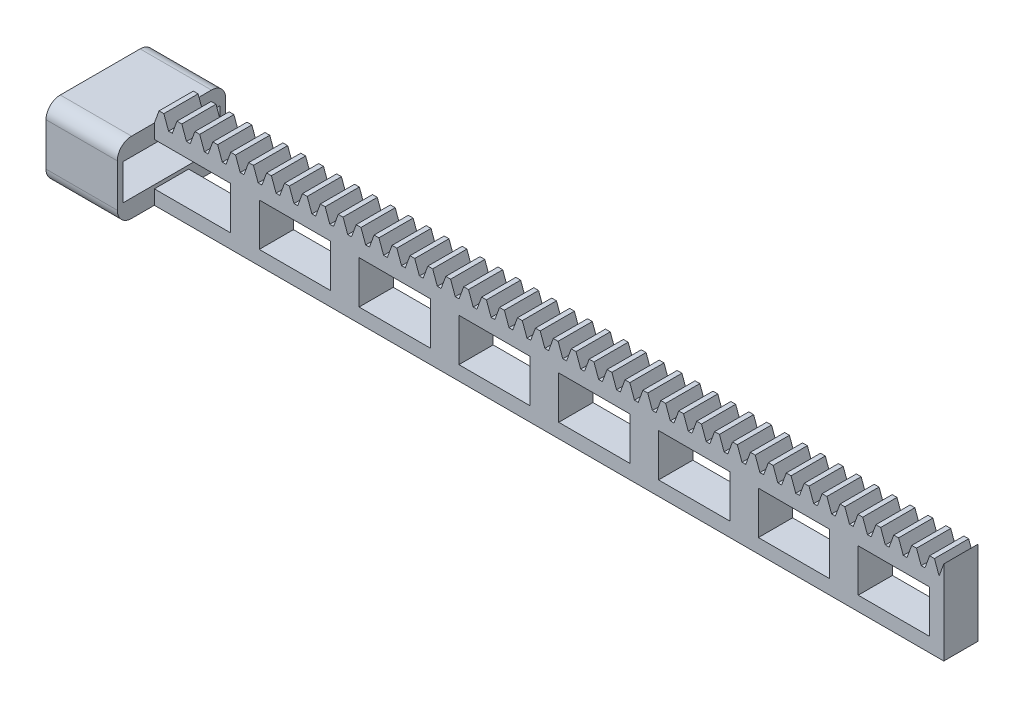
SolidWorks part; units mm, degrees
ref_plane "前视基准面" through (0, 0, 0) normal (0, 0, 1) x (1, 0, 0)
ref_plane "上视基准面" through (0, 0, 0) normal (0, 1, 0) x (1, 0, 0)
ref_plane "右视基准面" through (0, 0, 0) normal (1, 0, 0) x (0, 0, -1)
sketch "草图1" plane through (0, 0, 0) normal (0, 0, 1) x (1, 0, 0)
  line L1 (0, 0) -> (125.6637, 0)
  line L2 (0, 0) -> (0, -10)
  line L3 (0, -10) -> (125.6637, -10)
  line L4 (125.6637, 0) -> (125.6637, -10)
  dimension "D1" = 10
  dimension "L" = 125.6637
extrude "拉伸1" add sketch "草图1" along normal blind 30
sketch "草图2" plane through (0, 0, 30) normal (0, 0, 1) x (1, 0, 0)
  line L0 (0, 0) -> (1.6379, 4.5)
  line L1 (1.6379, 4.5) -> (3.3236, 4.5)
  line L2 (3.3236, 4.5) -> (4.9614, 0)
  line L3 (125.6637, 0) -> (0, 0) construction
  line L4 (0, 0) -> (4.9614, 0)
  line L5 (0.9099, 2.5) -> (4.0515, 2.5) construction
  dimension "D2" = 70
  dimension "alpha" = 110
  dimension "ha" = 2
  dimension "hf" = 2.5
  dimension "S" = 3.1416
extrude "拉伸2" add sketch "草图2" against normal up to surface (30 mm away) up to face at (62.8319, -5, 0)
pattern_linear "阵列(线性)1" count 20 spacing 6.2832 along (1, 0, 0) of "拉伸2"
sketch "草图3" plane through (0, 0, 30) normal (0, 0, 1) x (1, 0, 0)
  line L83 (0, 0) -> (0, -10)
  line L84 (0, -10) -> (125.6637, -10)
  line L85 (125.6637, -10) -> (125.6637, 0)
  line L86 (125.6637, 0) -> (124.342, 0)
  line L87 (124.342, 0) -> (122.7041, 4.5)
  line L88 (122.7041, 4.5) -> (121.0184, 4.5)
  line L89 (121.0184, 4.5) -> (119.3805, 0)
  line L90 (119.3805, 0) -> (118.0588, 0)
  line L91 (118.0588, 0) -> (116.4209, 4.5)
  line L92 (116.4209, 4.5) -> (114.7352, 4.5)
  line L93 (114.7352, 4.5) -> (113.0973, 0)
  line L94 (113.0973, 0) -> (111.7756, 0)
  line L95 (111.7756, 0) -> (110.1377, 4.5)
  line L96 (110.1377, 4.5) -> (108.452, 4.5)
  line L97 (108.452, 4.5) -> (106.8142, 0)
  line L98 (106.8142, 0) -> (105.4924, 0)
  line L99 (105.4924, 0) -> (103.8545, 4.5)
  line L100 (103.8545, 4.5) -> (102.1688, 4.5)
  line L101 (102.1688, 4.5) -> (100.531, 0)
  line L102 (100.531, 0) -> (99.2092, 0)
  line L103 (99.2092, 0) -> (97.5714, 4.5)
  line L104 (97.5714, 4.5) -> (95.8856, 4.5)
  line L105 (95.8856, 4.5) -> (94.2478, 0)
  line L106 (94.2478, 0) -> (92.926, 0)
  line L107 (92.926, 0) -> (91.2882, 4.5)
  line L108 (91.2882, 4.5) -> (89.6025, 4.5)
  line L109 (89.6025, 4.5) -> (87.9646, 0)
  line L110 (87.9646, 0) -> (86.6429, 0)
  line L111 (86.6429, 0) -> (85.005, 4.5)
  line L112 (85.005, 4.5) -> (83.3193, 4.5)
  line L113 (83.3193, 4.5) -> (81.6814, 0)
  line L114 (81.6814, 0) -> (80.3597, 0)
  line L115 (80.3597, 0) -> (78.7218, 4.5)
  line L116 (78.7218, 4.5) -> (77.0361, 4.5)
  line L117 (77.0361, 4.5) -> (75.3982, 0)
  line L118 (75.3982, 0) -> (74.0765, 0)
  line L119 (74.0765, 0) -> (72.4386, 4.5)
  line L120 (72.4386, 4.5) -> (70.7529, 4.5)
  line L121 (70.7529, 4.5) -> (69.115, 0)
  line L122 (69.115, 0) -> (67.7933, 0)
  line L123 (67.7933, 0) -> (66.1554, 4.5)
  line L124 (66.1554, 4.5) -> (64.4697, 4.5)
  line L125 (64.4697, 4.5) -> (62.8319, 0)
  line L126 (62.8319, 0) -> (61.5101, 0)
  line L127 (61.5101, 0) -> (59.8722, 4.5)
  line L128 (59.8722, 4.5) -> (58.1865, 4.5)
  line L129 (58.1865, 4.5) -> (56.5487, 0)
  line L130 (56.5487, 0) -> (55.2269, 0)
  line L131 (55.2269, 0) -> (53.5891, 4.5)
  line L132 (53.5891, 4.5) -> (51.9033, 4.5)
  line L133 (51.9033, 4.5) -> (50.2655, 0)
  line L134 (50.2655, 0) -> (48.9437, 0)
  line L135 (48.9437, 0) -> (47.3059, 4.5)
  line L136 (47.3059, 4.5) -> (45.6202, 4.5)
  line L137 (45.6202, 4.5) -> (43.9823, 0)
  line L138 (43.9823, 0) -> (42.6606, 0)
  line L139 (42.6606, 0) -> (41.0227, 4.5)
  line L140 (41.0227, 4.5) -> (39.337, 4.5)
  line L141 (39.337, 4.5) -> (37.6991, 0)
  line L142 (37.6991, 0) -> (36.3774, 0)
  line L143 (36.3774, 0) -> (34.7395, 4.5)
  line L144 (34.7395, 4.5) -> (33.0538, 4.5)
  line L145 (33.0538, 4.5) -> (31.4159, 0)
  line L146 (31.4159, 0) -> (30.0942, 0)
  line L147 (30.0942, 0) -> (28.4563, 4.5)
  line L148 (28.4563, 4.5) -> (26.7706, 4.5)
  line L149 (26.7706, 4.5) -> (25.1327, 0)
  line L150 (25.1327, 0) -> (23.811, 0)
  line L151 (23.811, 0) -> (22.1731, 4.5)
  line L152 (22.1731, 4.5) -> (20.4874, 4.5)
  line L153 (20.4874, 4.5) -> (18.8496, 0)
  line L154 (18.8496, 0) -> (17.5278, 0)
  line L155 (17.5278, 0) -> (15.8899, 4.5)
  line L156 (15.8899, 4.5) -> (14.2042, 4.5)
  line L157 (14.2042, 4.5) -> (12.5664, 0)
  line L158 (12.5664, 0) -> (11.2446, 0)
  line L159 (11.2446, 0) -> (9.6068, 4.5)
  line L160 (9.6068, 4.5) -> (7.9211, 4.5)
  line L161 (7.9211, 4.5) -> (6.2832, 0)
  line L162 (6.2832, 0) -> (4.9614, 0)
  line L163 (4.9614, 0) -> (3.3236, 4.5)
  line L164 (3.3236, 4.5) -> (1.6379, 4.5)
  line L165 (1.6379, 4.5) -> (0, 0)
  line L166 (0, 0) -> (0, -10)
  line L167 (0, -10) -> (125.6637, -10)
  line L168 (125.6637, -10) -> (125.6637, 0)
  line L169 (125.6637, 0) -> (124.342, 0)
  line L170 (124.342, 0) -> (122.7041, 4.5)
  line L171 (122.7041, 4.5) -> (121.0184, 4.5)
  line L172 (121.0184, 4.5) -> (119.3805, 0)
  line L173 (119.3805, 0) -> (118.0588, 0)
  line L174 (118.0588, 0) -> (116.4209, 4.5)
  line L175 (116.4209, 4.5) -> (114.7352, 4.5)
  line L176 (114.7352, 4.5) -> (113.0973, 0)
  line L177 (113.0973, 0) -> (111.7756, 0)
  line L178 (111.7756, 0) -> (110.1377, 4.5)
  line L179 (110.1377, 4.5) -> (108.452, 4.5)
  line L180 (108.452, 4.5) -> (106.8142, 0)
  line L181 (106.8142, 0) -> (105.4924, 0)
  line L182 (105.4924, 0) -> (103.8545, 4.5)
  line L183 (103.8545, 4.5) -> (102.1688, 4.5)
  line L184 (102.1688, 4.5) -> (100.531, 0)
  line L185 (100.531, 0) -> (99.2092, 0)
  line L186 (99.2092, 0) -> (97.5714, 4.5)
  line L187 (97.5714, 4.5) -> (95.8856, 4.5)
  line L188 (95.8856, 4.5) -> (94.2478, 0)
  line L189 (94.2478, 0) -> (92.926, 0)
  line L190 (92.926, 0) -> (91.2882, 4.5)
  line L191 (91.2882, 4.5) -> (89.6025, 4.5)
  line L192 (89.6025, 4.5) -> (87.9646, 0)
  line L193 (87.9646, 0) -> (86.6429, 0)
  line L194 (86.6429, 0) -> (85.005, 4.5)
  line L195 (85.005, 4.5) -> (83.3193, 4.5)
  line L196 (83.3193, 4.5) -> (81.6814, 0)
  line L197 (81.6814, 0) -> (80.3597, 0)
  line L198 (80.3597, 0) -> (78.7218, 4.5)
  line L199 (78.7218, 4.5) -> (77.0361, 4.5)
  line L200 (77.0361, 4.5) -> (75.3982, 0)
  line L201 (75.3982, 0) -> (74.0765, 0)
  line L202 (74.0765, 0) -> (72.4386, 4.5)
  line L203 (72.4386, 4.5) -> (70.7529, 4.5)
  line L204 (70.7529, 4.5) -> (69.115, 0)
  line L205 (69.115, 0) -> (67.7933, 0)
  line L206 (67.7933, 0) -> (66.1554, 4.5)
  line L207 (66.1554, 4.5) -> (64.4697, 4.5)
  line L208 (64.4697, 4.5) -> (62.8319, 0)
  line L209 (62.8319, 0) -> (61.5101, 0)
  line L210 (61.5101, 0) -> (59.8722, 4.5)
  line L211 (59.8722, 4.5) -> (58.1865, 4.5)
  line L212 (58.1865, 4.5) -> (56.5487, 0)
  line L213 (56.5487, 0) -> (55.2269, 0)
  line L214 (55.2269, 0) -> (53.5891, 4.5)
  line L215 (53.5891, 4.5) -> (51.9033, 4.5)
  line L216 (51.9033, 4.5) -> (50.2655, 0)
  line L217 (50.2655, 0) -> (48.9437, 0)
  line L218 (48.9437, 0) -> (47.3059, 4.5)
  line L219 (47.3059, 4.5) -> (45.6202, 4.5)
  line L220 (45.6202, 4.5) -> (43.9823, 0)
  line L221 (43.9823, 0) -> (42.6606, 0)
  line L222 (42.6606, 0) -> (41.0227, 4.5)
  line L223 (41.0227, 4.5) -> (39.337, 4.5)
  line L224 (39.337, 4.5) -> (37.6991, 0)
  line L225 (37.6991, 0) -> (36.3774, 0)
  line L226 (36.3774, 0) -> (34.7395, 4.5)
  line L227 (34.7395, 4.5) -> (33.0538, 4.5)
  line L228 (33.0538, 4.5) -> (31.4159, 0)
  line L229 (31.4159, 0) -> (30.0942, 0)
  line L230 (30.0942, 0) -> (28.4563, 4.5)
  line L231 (28.4563, 4.5) -> (26.7706, 4.5)
  line L232 (26.7706, 4.5) -> (25.1327, 0)
  line L233 (25.1327, 0) -> (23.811, 0)
  line L234 (23.811, 0) -> (22.1731, 4.5)
  line L235 (22.1731, 4.5) -> (20.4874, 4.5)
  line L236 (20.4874, 4.5) -> (18.8496, 0)
  line L237 (18.8496, 0) -> (17.5278, 0)
  line L238 (17.5278, 0) -> (15.8899, 4.5)
  line L239 (15.8899, 4.5) -> (14.2042, 4.5)
  line L240 (14.2042, 4.5) -> (12.5664, 0)
  line L241 (12.5664, 0) -> (11.2446, 0)
  line L242 (11.2446, 0) -> (9.6068, 4.5)
  line L243 (9.6068, 4.5) -> (7.9211, 4.5)
  line L244 (7.9211, 4.5) -> (6.2832, 0)
  line L245 (6.2832, 0) -> (4.9614, 0)
  line L246 (4.9614, 0) -> (3.3236, 4.5)
  line L247 (3.3236, 4.5) -> (1.6379, 4.5)
  line L248 (1.6379, 4.5) -> (0, 0)
  dimension "D1" = 0
extrude "切除-拉伸1" cut sketch "草图3" against normal blind 22
sketch "草图4" plane through (0, 0, 0) normal (0, 0, -1) x (-1, 0, 0)
  line L0 (-121.8612, 4.5) -> (-121.8612, -10)
  line L1 (-121.0184, 4.5) -> (-122.7041, 4.5) construction
  line L2 (0, -10) -> (-125.6637, -10) construction
  line L3 (-125.6637, 0) -> (-124.342, 0) construction
  line L4 (-125.6637, -10) -> (-125.6637, 0) construction
  line L5 (-122.7041, 4.5) -> (-124.342, 0) construction
  line L6 (-121.8612, -10) -> (-125.6637, -10)
  line L7 (-125.6637, 0) -> (-124.342, 0)
  line L8 (-125.6637, -10) -> (-125.6637, 0)
  line L9 (-121.8612, 4.5) -> (-122.7041, 4.5)
  line L10 (-122.7041, 4.5) -> (-124.342, 0)
extrude "切除-拉伸2" cut sketch "草图4" against normal up to next
mirror "镜向1" about plane through (121.8612, 4.5, 8.001) normal (-1, 0, 0) of bodies 105
sketch "草图5" plane through (0, 0, 0) normal (0, 0, -1) x (-1, 0, 0)
  line L0 (-241.2418, 4.5) -> (-241.2418, -10)
  line L1 (-242.0846, 4.5) -> (-240.3989, 4.5) construction
  line L2 (0, -10) -> (-243.7225, -10) construction
  line L3 (-243.7225, 0) -> (-242.0846, 4.5) construction
  line L4 (-243.7225, 0) -> (-243.7225, -10) construction
  line L5 (-241.2418, -10) -> (-243.7225, -10)
  line L6 (-242.0846, 4.5) -> (-241.2418, 4.5)
  line L7 (-243.7225, 0) -> (-242.0846, 4.5)
  line L8 (-243.7225, 0) -> (-243.7225, -10)
extrude "切除-拉伸3" cut sketch "草图5" against normal up to next
mirror "镜向2" about plane through (241.2418, 4.5, 8.001) normal (-1, 0, 0) of bodies 107
sketch "草图7" plane through (0, 0, 0) normal (0, 0, -1) x (-1, 0, 0)
  line L1 (-275.1384, 4.5785) -> (-482.4835, 4.5785)
  line L2 (-275.1384, 4.5785) -> (-275.1384, -10)
  line L3 (-275.1384, -10) -> (-482.4835, -10)
  line L4 (-482.4835, 4.5785) -> (-482.4835, -10)
extrude "切除-拉伸6" cut sketch "草图7" against normal up to next
mirror "镜向4" about plane through (275.1384, 4.5785, 8.001) normal (-1, 0, 0) of bodies 112
sketch "草图9" plane through (0, 0, 0) normal (0, 0, -1) x (-1, 0, 0)
  line L1 (-276.7763, 5.2464) -> (-555.7489, 5.2464)
  line L2 (-276.7763, 5.2464) -> (-276.7763, -13.7938)
  line L3 (-276.7763, -13.7938) -> (-555.7489, -13.7938)
  line L4 (-555.7489, 5.2464) -> (-555.7489, -13.7938)
extrude "切除-拉伸7" cut sketch "草图9" against normal up to next
sketch "草图10" plane through (0, 0, 0) normal (-1, 0, 0) x (0, 0, 1)
  line L0 (8, 0) -> (8, -10) construction
  line L1 (0, -10) -> (8, -10)
  line L2 (0, -10) -> (0, -25)
  line L3 (0, -25) -> (8, -25)
  line L4 (8, -10) -> (8, -25)
  dimension "D1" = 15
extrude "凸台-拉伸1" add sketch "草图10" along direction (-1, 0, 0) on the side against the normal up to surface (276.7763 mm away) up to face at (276.7763, -2.75, 4)
sketch "草图11" plane through (0, 0, 0) normal (-1, 0, 0) x (0, 0, 1)
  line L0 (-15, 0) -> (23, 0)
  line L1 (-15, 0) -> (-15, -25)
  line L2 (-15, -25) -> (23, -25)
  line L3 (23, 0) -> (23, -25)
  line L4 (4, 0) -> (4, -25) construction
  line L5 (-15, -12.5) -> (-16.4648, -12.5) construction
  line L6 (0, -12.5) -> (2.4226, -12.5)
  line L7 (0, 0) -> (0, -25) construction
  line L8 (0, -25) -> (8, -25) construction
  circle A0 centre (-10, -16) radius 1.25
  circle A1 centre (-10, -9) radius 1.25
  circle A2 centre (18, -9) radius 1.25
  circle A3 centre (18, -16) radius 1.25
  point P3 (4, -25)
  dimension "D3" = 2.5
  dimension "D1" = 28
  dimension "D2" = 7
  dimension "D4" = 5
  dimension "D5" = 9
  dimension "D6" = 5
  dimension "D7" = 9
extrude "凸台-拉伸2" add sketch "草图11" along normal blind 25 contours L0 L3 L2 L1 | A1 | A3 | A2 | A0
sketch "草图18" plane through (0, 0, 8) normal (0, 0, 1) x (1, 0, 0)
  line L179 (276.7763, -25) -> (276.7763, 4.5)
  line L180 (276.7763, 4.5) -> (275.1384, 0)
  line L181 (275.1384, 0) -> (273.5005, 4.5)
  line L182 (273.5005, 4.5) -> (271.8148, 4.5)
  line L183 (271.8148, 4.5) -> (270.177, 0)
  line L184 (270.177, 0) -> (268.8552, 0)
  line L185 (268.8552, 0) -> (267.2174, 4.5)
  line L186 (267.2174, 4.5) -> (265.5316, 4.5)
  line L187 (265.5316, 4.5) -> (263.8938, 0)
  line L188 (263.8938, 0) -> (262.572, 0)
  line L189 (262.572, 0) -> (260.9342, 4.5)
  line L190 (260.9342, 4.5) -> (259.2485, 4.5)
  line L191 (259.2485, 4.5) -> (257.6106, 0)
  line L192 (257.6106, 0) -> (256.2889, 0)
  line L193 (256.2889, 0) -> (254.651, 4.5)
  line L194 (254.651, 4.5) -> (252.9653, 4.5)
  line L195 (252.9653, 4.5) -> (251.3274, 0)
  line L196 (251.3274, 0) -> (250.0057, 0)
  line L197 (250.0057, 0) -> (248.3678, 4.5)
  line L198 (248.3678, 4.5) -> (246.6821, 4.5)
  line L199 (246.6821, 4.5) -> (245.0442, 0)
  line L200 (245.0442, 0) -> (243.7225, 0)
  line L201 (243.7225, 0) -> (242.0846, 4.5)
  line L202 (242.0846, 4.5) -> (240.3989, 4.5)
  line L203 (240.3989, 4.5) -> (238.761, 0)
  line L204 (238.761, 0) -> (237.4393, 0)
  line L205 (237.4393, 0) -> (235.8014, 4.5)
  line L206 (235.8014, 4.5) -> (234.1157, 4.5)
  line L207 (234.1157, 4.5) -> (232.4779, 0)
  line L208 (232.4779, 0) -> (231.1561, 0)
  line L209 (231.1561, 0) -> (229.5182, 4.5)
  line L210 (229.5182, 4.5) -> (227.8325, 4.5)
  line L211 (227.8325, 4.5) -> (226.1947, 0)
  line L212 (226.1947, 0) -> (224.8729, 0)
  line L213 (224.8729, 0) -> (223.2351, 4.5)
  line L214 (223.2351, 4.5) -> (221.5494, 4.5)
  line L215 (221.5494, 4.5) -> (219.9115, 0)
  line L216 (219.9115, 0) -> (218.5897, 0)
  line L217 (218.5897, 0) -> (216.9519, 4.5)
  line L218 (216.9519, 4.5) -> (215.2662, 4.5)
  line L219 (215.2662, 4.5) -> (213.6283, 0)
  line L220 (213.6283, 0) -> (212.3066, 0)
  line L221 (212.3066, 0) -> (210.6687, 4.5)
  line L222 (210.6687, 4.5) -> (208.983, 4.5)
  line L223 (208.983, 4.5) -> (207.3451, 0)
  line L224 (207.3451, 0) -> (206.0234, 0)
  line L225 (206.0234, 0) -> (204.3855, 4.5)
  line L226 (204.3855, 4.5) -> (202.6998, 4.5)
  line L227 (202.6998, 4.5) -> (201.0619, 0)
  line L228 (201.0619, 0) -> (199.7402, 0)
  line L229 (199.7402, 0) -> (198.1023, 4.5)
  line L230 (198.1023, 4.5) -> (196.4166, 4.5)
  line L231 (196.4166, 4.5) -> (194.7787, 0)
  line L232 (194.7787, 0) -> (193.457, 0)
  line L233 (193.457, 0) -> (191.8191, 4.5)
  line L234 (191.8191, 4.5) -> (190.1334, 4.5)
  line L235 (190.1334, 4.5) -> (188.4956, 0)
  line L236 (188.4956, 0) -> (187.1738, 0)
  line L237 (187.1738, 0) -> (185.536, 4.5)
  line L238 (185.536, 4.5) -> (183.8502, 4.5)
  line L239 (183.8502, 4.5) -> (182.2124, 0)
  line L240 (182.2124, 0) -> (180.8906, 0)
  line L241 (180.8906, 0) -> (179.2528, 4.5)
  line L242 (179.2528, 4.5) -> (177.5671, 4.5)
  line L243 (177.5671, 4.5) -> (175.9292, 0)
  line L244 (175.9292, 0) -> (174.6074, 0)
  line L245 (174.6074, 0) -> (172.9696, 4.5)
  line L246 (172.9696, 4.5) -> (171.2839, 4.5)
  line L247 (171.2839, 4.5) -> (169.646, 0)
  line L248 (169.646, 0) -> (168.3243, 0)
  line L249 (168.3243, 0) -> (166.6864, 4.5)
  line L250 (166.6864, 4.5) -> (165.0007, 4.5)
  line L251 (165.0007, 4.5) -> (163.3628, 0)
  line L252 (163.3628, 0) -> (162.0411, 0)
  line L253 (162.0411, 0) -> (160.4032, 4.5)
  line L254 (160.4032, 4.5) -> (158.7175, 4.5)
  line L255 (158.7175, 4.5) -> (157.0796, 0)
  line L256 (157.0796, 0) -> (155.7579, 0)
  line L257 (155.7579, 0) -> (154.12, 4.5)
  line L258 (154.12, 4.5) -> (152.4343, 4.5)
  line L259 (152.4343, 4.5) -> (150.7964, 0)
  line L260 (150.7964, 0) -> (149.4747, 0)
  line L261 (149.4747, 0) -> (147.8368, 4.5)
  line L262 (147.8368, 4.5) -> (146.1511, 4.5)
  line L263 (146.1511, 4.5) -> (144.5133, 0)
  line L264 (144.5133, 0) -> (143.1915, 0)
  line L265 (143.1915, 0) -> (141.5537, 4.5)
  line L266 (141.5537, 4.5) -> (139.8679, 4.5)
  line L267 (139.8679, 4.5) -> (138.2301, 0)
  line L268 (138.2301, 0) -> (136.9083, 0)
  line L269 (136.9083, 0) -> (135.2705, 4.5)
  line L270 (135.2705, 4.5) -> (133.5848, 4.5)
  line L271 (133.5848, 4.5) -> (131.9469, 0)
  line L272 (131.9469, 0) -> (130.6251, 0)
  line L273 (130.6251, 0) -> (128.9873, 4.5)
  line L274 (128.9873, 4.5) -> (127.3016, 4.5)
  line L275 (127.3016, 4.5) -> (125.6637, 0)
  line L276 (125.6637, 0) -> (124.342, 0)
  line L277 (124.342, 0) -> (122.7041, 4.5)
  line L278 (122.7041, 4.5) -> (121.0184, 4.5)
  line L279 (121.0184, 4.5) -> (119.3805, 0)
  line L280 (119.3805, 0) -> (118.0588, 0)
  line L281 (118.0588, 0) -> (116.4209, 4.5)
  line L282 (116.4209, 4.5) -> (114.7352, 4.5)
  line L283 (114.7352, 4.5) -> (113.0973, 0)
  line L284 (113.0973, 0) -> (111.7756, 0)
  line L285 (111.7756, 0) -> (110.1377, 4.5)
  line L286 (110.1377, 4.5) -> (108.452, 4.5)
  line L287 (108.452, 4.5) -> (106.8142, 0)
  line L288 (106.8142, 0) -> (105.4924, 0)
  line L289 (105.4924, 0) -> (103.8545, 4.5)
  line L290 (103.8545, 4.5) -> (102.1688, 4.5)
  line L291 (102.1688, 4.5) -> (100.531, 0)
  line L292 (100.531, 0) -> (99.2092, 0)
  line L293 (99.2092, 0) -> (97.5714, 4.5)
  line L294 (97.5714, 4.5) -> (95.8856, 4.5)
  line L295 (95.8856, 4.5) -> (94.2478, 0)
  line L296 (94.2478, 0) -> (92.926, 0)
  line L297 (92.926, 0) -> (91.2882, 4.5)
  line L298 (91.2882, 4.5) -> (89.6025, 4.5)
  line L299 (89.6025, 4.5) -> (87.9646, 0)
  line L300 (87.9646, 0) -> (86.6429, 0)
  line L301 (86.6429, 0) -> (85.005, 4.5)
  line L302 (85.005, 4.5) -> (83.3193, 4.5)
  line L303 (83.3193, 4.5) -> (81.6814, 0)
  line L304 (81.6814, 0) -> (80.3597, 0)
  line L305 (80.3597, 0) -> (78.7218, 4.5)
  line L306 (78.7218, 4.5) -> (77.0361, 4.5)
  line L307 (77.0361, 4.5) -> (75.3982, 0)
  line L308 (75.3982, 0) -> (74.0765, 0)
  line L309 (74.0765, 0) -> (72.4386, 4.5)
  line L310 (72.4386, 4.5) -> (70.7529, 4.5)
  line L311 (70.7529, 4.5) -> (69.115, 0)
  line L312 (69.115, 0) -> (67.7933, 0)
  line L313 (67.7933, 0) -> (66.1554, 4.5)
  line L314 (66.1554, 4.5) -> (64.4697, 4.5)
  line L315 (64.4697, 4.5) -> (62.8319, 0)
  line L316 (62.8319, 0) -> (61.5101, 0)
  line L317 (61.5101, 0) -> (59.8722, 4.5)
  line L318 (59.8722, 4.5) -> (58.1865, 4.5)
  line L319 (58.1865, 4.5) -> (56.5487, 0)
  line L320 (56.5487, 0) -> (55.2269, 0)
  line L321 (55.2269, 0) -> (53.5891, 4.5)
  line L322 (53.5891, 4.5) -> (51.9033, 4.5)
  line L323 (51.9033, 4.5) -> (50.2655, 0)
  line L324 (50.2655, 0) -> (48.9437, 0)
  line L325 (48.9437, 0) -> (47.3059, 4.5)
  line L326 (47.3059, 4.5) -> (45.6202, 4.5)
  line L327 (45.6202, 4.5) -> (43.9823, 0)
  line L328 (43.9823, 0) -> (42.6606, 0)
  line L329 (42.6606, 0) -> (41.0227, 4.5)
  line L330 (41.0227, 4.5) -> (39.337, 4.5)
  line L331 (39.337, 4.5) -> (37.6991, 0)
  line L332 (37.6991, 0) -> (36.3774, 0)
  line L333 (36.3774, 0) -> (34.7395, 4.5)
  line L334 (34.7395, 4.5) -> (33.0538, 4.5)
  line L335 (33.0538, 4.5) -> (31.4159, 0)
  line L336 (31.4159, 0) -> (30.0942, 0)
  line L337 (30.0942, 0) -> (28.4563, 4.5)
  line L338 (28.4563, 4.5) -> (26.7706, 4.5)
  line L339 (26.7706, 4.5) -> (25.1327, 0)
  line L340 (25.1327, 0) -> (23.811, 0)
  line L341 (23.811, 0) -> (22.1731, 4.5)
  line L342 (22.1731, 4.5) -> (20.4874, 4.5)
  line L343 (20.4874, 4.5) -> (18.8496, 0)
  line L344 (18.8496, 0) -> (17.5278, 0)
  line L345 (17.5278, 0) -> (15.8899, 4.5)
  line L346 (15.8899, 4.5) -> (14.2042, 4.5)
  line L347 (14.2042, 4.5) -> (12.5664, 0)
  line L348 (12.5664, 0) -> (11.2446, 0)
  line L349 (11.2446, 0) -> (9.6068, 4.5)
  line L350 (9.6068, 4.5) -> (7.9211, 4.5)
  line L351 (7.9211, 4.5) -> (6.2832, 0)
  line L352 (6.2832, 0) -> (4.9614, 0)
  line L353 (4.9614, 0) -> (3.3236, 4.5)
  line L354 (3.3236, 4.5) -> (1.6379, 4.5)
  line L355 (1.6379, 4.5) -> (0, 0)
  line L356 (0, 0) -> (0, -25)
  line L357 (0, -25) -> (276.7763, -25)
  line L358 (276.7763, -25) -> (276.7763, 4.5)
  line L359 (276.7763, 4.5) -> (275.1384, 0)
  line L360 (275.1384, 0) -> (273.5005, 4.5)
  line L361 (273.5005, 4.5) -> (271.8148, 4.5)
  line L362 (271.8148, 4.5) -> (270.177, 0)
  line L363 (270.177, 0) -> (268.8552, 0)
  line L364 (268.8552, 0) -> (267.2174, 4.5)
  line L365 (267.2174, 4.5) -> (265.5316, 4.5)
  line L366 (265.5316, 4.5) -> (263.8938, 0)
  line L367 (263.8938, 0) -> (262.572, 0)
  line L368 (262.572, 0) -> (260.9342, 4.5)
  line L369 (260.9342, 4.5) -> (259.2485, 4.5)
  line L370 (259.2485, 4.5) -> (257.6106, 0)
  line L371 (257.6106, 0) -> (256.2889, 0)
  line L372 (256.2889, 0) -> (254.651, 4.5)
  line L373 (254.651, 4.5) -> (252.9653, 4.5)
  line L374 (252.9653, 4.5) -> (251.3274, 0)
  line L375 (251.3274, 0) -> (250.0057, 0)
  line L376 (250.0057, 0) -> (248.3678, 4.5)
  line L377 (248.3678, 4.5) -> (246.6821, 4.5)
  line L378 (246.6821, 4.5) -> (245.0442, 0)
  line L379 (245.0442, 0) -> (243.7225, 0)
  line L380 (243.7225, 0) -> (242.0846, 4.5)
  line L381 (242.0846, 4.5) -> (240.3989, 4.5)
  line L382 (240.3989, 4.5) -> (238.761, 0)
  line L383 (238.761, 0) -> (237.4393, 0)
  line L384 (237.4393, 0) -> (235.8014, 4.5)
  line L385 (235.8014, 4.5) -> (234.1157, 4.5)
  line L386 (234.1157, 4.5) -> (232.4779, 0)
  line L387 (232.4779, 0) -> (231.1561, 0)
  line L388 (231.1561, 0) -> (229.5182, 4.5)
  line L389 (229.5182, 4.5) -> (227.8325, 4.5)
  line L390 (227.8325, 4.5) -> (226.1947, 0)
  line L391 (226.1947, 0) -> (224.8729, 0)
  line L392 (224.8729, 0) -> (223.2351, 4.5)
  line L393 (223.2351, 4.5) -> (221.5494, 4.5)
  line L394 (221.5494, 4.5) -> (219.9115, 0)
  line L395 (219.9115, 0) -> (218.5897, 0)
  line L396 (218.5897, 0) -> (216.9519, 4.5)
  line L397 (216.9519, 4.5) -> (215.2662, 4.5)
  line L398 (215.2662, 4.5) -> (213.6283, 0)
  line L399 (213.6283, 0) -> (212.3066, 0)
  line L400 (212.3066, 0) -> (210.6687, 4.5)
  line L401 (210.6687, 4.5) -> (208.983, 4.5)
  line L402 (208.983, 4.5) -> (207.3451, 0)
  line L403 (207.3451, 0) -> (206.0234, 0)
  line L404 (206.0234, 0) -> (204.3855, 4.5)
  line L405 (204.3855, 4.5) -> (202.6998, 4.5)
  line L406 (202.6998, 4.5) -> (201.0619, 0)
  line L407 (201.0619, 0) -> (199.7402, 0)
  line L408 (199.7402, 0) -> (198.1023, 4.5)
  line L409 (198.1023, 4.5) -> (196.4166, 4.5)
  line L410 (196.4166, 4.5) -> (194.7787, 0)
  line L411 (194.7787, 0) -> (193.457, 0)
  line L412 (193.457, 0) -> (191.8191, 4.5)
  line L413 (191.8191, 4.5) -> (190.1334, 4.5)
  line L414 (190.1334, 4.5) -> (188.4956, 0)
  line L415 (188.4956, 0) -> (187.1738, 0)
  line L416 (187.1738, 0) -> (185.536, 4.5)
  line L417 (185.536, 4.5) -> (183.8502, 4.5)
  line L418 (183.8502, 4.5) -> (182.2124, 0)
  line L419 (182.2124, 0) -> (180.8906, 0)
  line L420 (180.8906, 0) -> (179.2528, 4.5)
  line L421 (179.2528, 4.5) -> (177.5671, 4.5)
  line L422 (177.5671, 4.5) -> (175.9292, 0)
  line L423 (175.9292, 0) -> (174.6074, 0)
  line L424 (174.6074, 0) -> (172.9696, 4.5)
  line L425 (172.9696, 4.5) -> (171.2839, 4.5)
  line L426 (171.2839, 4.5) -> (169.646, 0)
  line L427 (169.646, 0) -> (168.3243, 0)
  line L428 (168.3243, 0) -> (166.6864, 4.5)
  line L429 (166.6864, 4.5) -> (165.0007, 4.5)
  line L430 (165.0007, 4.5) -> (163.3628, 0)
  line L431 (163.3628, 0) -> (162.0411, 0)
  line L432 (162.0411, 0) -> (160.4032, 4.5)
  line L433 (160.4032, 4.5) -> (158.7175, 4.5)
  line L434 (158.7175, 4.5) -> (157.0796, 0)
  line L435 (157.0796, 0) -> (155.7579, 0)
  line L436 (155.7579, 0) -> (154.12, 4.5)
  line L437 (154.12, 4.5) -> (152.4343, 4.5)
  line L438 (152.4343, 4.5) -> (150.7964, 0)
  line L439 (150.7964, 0) -> (149.4747, 0)
  line L440 (149.4747, 0) -> (147.8368, 4.5)
  line L441 (147.8368, 4.5) -> (146.1511, 4.5)
  line L442 (146.1511, 4.5) -> (144.5133, 0)
  line L443 (144.5133, 0) -> (143.1915, 0)
  line L444 (143.1915, 0) -> (141.5537, 4.5)
  line L445 (141.5537, 4.5) -> (139.8679, 4.5)
  line L446 (139.8679, 4.5) -> (138.2301, 0)
  line L447 (138.2301, 0) -> (136.9083, 0)
  line L448 (136.9083, 0) -> (135.2705, 4.5)
  line L449 (135.2705, 4.5) -> (133.5848, 4.5)
  line L450 (133.5848, 4.5) -> (131.9469, 0)
  line L451 (131.9469, 0) -> (130.6251, 0)
  line L452 (130.6251, 0) -> (128.9873, 4.5)
  line L453 (128.9873, 4.5) -> (127.3016, 4.5)
  line L454 (127.3016, 4.5) -> (125.6637, 0)
  line L455 (125.6637, 0) -> (124.342, 0)
  line L456 (124.342, 0) -> (122.7041, 4.5)
  line L457 (122.7041, 4.5) -> (121.0184, 4.5)
  line L458 (121.0184, 4.5) -> (119.3805, 0)
  line L459 (119.3805, 0) -> (118.0588, 0)
  line L460 (118.0588, 0) -> (116.4209, 4.5)
  line L461 (116.4209, 4.5) -> (114.7352, 4.5)
  line L462 (114.7352, 4.5) -> (113.0973, 0)
  line L463 (113.0973, 0) -> (111.7756, 0)
  line L464 (111.7756, 0) -> (110.1377, 4.5)
  line L465 (110.1377, 4.5) -> (108.452, 4.5)
  line L466 (108.452, 4.5) -> (106.8142, 0)
  line L467 (106.8142, 0) -> (105.4924, 0)
  line L468 (105.4924, 0) -> (103.8545, 4.5)
  line L469 (103.8545, 4.5) -> (102.1688, 4.5)
  line L470 (102.1688, 4.5) -> (100.531, 0)
  line L471 (100.531, 0) -> (99.2092, 0)
  line L472 (99.2092, 0) -> (97.5714, 4.5)
  line L473 (97.5714, 4.5) -> (95.8856, 4.5)
  line L474 (95.8856, 4.5) -> (94.2478, 0)
  line L475 (94.2478, 0) -> (92.926, 0)
  line L476 (92.926, 0) -> (91.2882, 4.5)
  line L477 (91.2882, 4.5) -> (89.6025, 4.5)
  line L478 (89.6025, 4.5) -> (87.9646, 0)
  line L479 (87.9646, 0) -> (86.6429, 0)
  line L480 (86.6429, 0) -> (85.005, 4.5)
  line L481 (85.005, 4.5) -> (83.3193, 4.5)
  line L482 (83.3193, 4.5) -> (81.6814, 0)
  line L483 (81.6814, 0) -> (80.3597, 0)
  line L484 (80.3597, 0) -> (78.7218, 4.5)
  line L485 (78.7218, 4.5) -> (77.0361, 4.5)
  line L486 (77.0361, 4.5) -> (75.3982, 0)
  line L487 (75.3982, 0) -> (74.0765, 0)
  line L488 (74.0765, 0) -> (72.4386, 4.5)
  line L489 (72.4386, 4.5) -> (70.7529, 4.5)
  line L490 (70.7529, 4.5) -> (69.115, 0)
  line L491 (69.115, 0) -> (67.7933, 0)
  line L492 (67.7933, 0) -> (66.1554, 4.5)
  line L493 (66.1554, 4.5) -> (64.4697, 4.5)
  line L494 (64.4697, 4.5) -> (62.8319, 0)
  line L495 (62.8319, 0) -> (61.5101, 0)
  line L496 (61.5101, 0) -> (59.8722, 4.5)
  line L497 (59.8722, 4.5) -> (58.1865, 4.5)
  line L498 (58.1865, 4.5) -> (56.5487, 0)
  line L499 (56.5487, 0) -> (55.2269, 0)
  line L500 (55.2269, 0) -> (53.5891, 4.5)
  line L501 (53.5891, 4.5) -> (51.9033, 4.5)
  line L502 (51.9033, 4.5) -> (50.2655, 0)
  line L503 (50.2655, 0) -> (48.9437, 0)
  line L504 (48.9437, 0) -> (47.3059, 4.5)
  line L505 (47.3059, 4.5) -> (45.6202, 4.5)
  line L506 (45.6202, 4.5) -> (43.9823, 0)
  line L507 (43.9823, 0) -> (42.6606, 0)
  line L508 (42.6606, 0) -> (41.0227, 4.5)
  line L509 (41.0227, 4.5) -> (39.337, 4.5)
  line L510 (39.337, 4.5) -> (37.6991, 0)
  line L511 (37.6991, 0) -> (36.3774, 0)
  line L512 (36.3774, 0) -> (34.7395, 4.5)
  line L513 (34.7395, 4.5) -> (33.0538, 4.5)
  line L514 (33.0538, 4.5) -> (31.4159, 0)
  line L515 (31.4159, 0) -> (30.0942, 0)
  line L516 (30.0942, 0) -> (28.4563, 4.5)
  line L517 (28.4563, 4.5) -> (26.7706, 4.5)
  line L518 (26.7706, 4.5) -> (25.1327, 0)
  line L519 (25.1327, 0) -> (23.811, 0)
  line L520 (23.811, 0) -> (22.1731, 4.5)
  line L521 (22.1731, 4.5) -> (20.4874, 4.5)
  line L522 (20.4874, 4.5) -> (18.8496, 0)
  line L523 (18.8496, 0) -> (17.5278, 0)
  line L524 (17.5278, 0) -> (15.8899, 4.5)
  line L525 (15.8899, 4.5) -> (14.2042, 4.5)
  line L526 (14.2042, 4.5) -> (12.5664, 0)
  line L527 (12.5664, 0) -> (11.2446, 0)
  line L528 (11.2446, 0) -> (9.6068, 4.5)
  line L529 (9.6068, 4.5) -> (7.9211, 4.5)
  line L530 (7.9211, 4.5) -> (6.2832, 0)
  line L531 (6.2832, 0) -> (4.9614, 0)
  line L532 (4.9614, 0) -> (3.3236, 4.5)
  line L533 (3.3236, 4.5) -> (1.6379, 4.5)
  line L534 (1.6379, 4.5) -> (0, 0)
  line L535 (0, 0) -> (0, -25)
  line L536 (0, -25) -> (276.7763, -25)
  dimension "D1" = 0
sketch "草图19" plane through (0, 0, 0) normal (0, 0, -1) x (-1, 0, 0)
  line L179 (-275.1384, 0) -> (-276.7763, 4.5)
  line L180 (-276.7763, 4.5) -> (-276.7763, -25)
  line L181 (-276.7763, -25) -> (0, -25)
  line L182 (0, -25) -> (0, 0)
  line L183 (0, 0) -> (-1.6379, 4.5)
  line L184 (-1.6379, 4.5) -> (-3.3236, 4.5)
  line L185 (-3.3236, 4.5) -> (-4.9614, 0)
  line L186 (-4.9614, 0) -> (-6.2832, 0)
  line L187 (-6.2832, 0) -> (-7.9211, 4.5)
  line L188 (-7.9211, 4.5) -> (-9.6068, 4.5)
  line L189 (-9.6068, 4.5) -> (-11.2446, 0)
  line L190 (-11.2446, 0) -> (-12.5664, 0)
  line L191 (-12.5664, 0) -> (-14.2042, 4.5)
  line L192 (-14.2042, 4.5) -> (-15.8899, 4.5)
  line L193 (-15.8899, 4.5) -> (-17.5278, 0)
  line L194 (-17.5278, 0) -> (-18.8496, 0)
  line L195 (-18.8496, 0) -> (-20.4874, 4.5)
  line L196 (-20.4874, 4.5) -> (-22.1731, 4.5)
  line L197 (-22.1731, 4.5) -> (-23.811, 0)
  line L198 (-23.811, 0) -> (-25.1327, 0)
  line L199 (-25.1327, 0) -> (-26.7706, 4.5)
  line L200 (-26.7706, 4.5) -> (-28.4563, 4.5)
  line L201 (-28.4563, 4.5) -> (-30.0942, 0)
  line L202 (-30.0942, 0) -> (-31.4159, 0)
  line L203 (-31.4159, 0) -> (-33.0538, 4.5)
  line L204 (-33.0538, 4.5) -> (-34.7395, 4.5)
  line L205 (-34.7395, 4.5) -> (-36.3774, 0)
  line L206 (-36.3774, 0) -> (-37.6991, 0)
  line L207 (-37.6991, 0) -> (-39.337, 4.5)
  line L208 (-39.337, 4.5) -> (-41.0227, 4.5)
  line L209 (-41.0227, 4.5) -> (-42.6606, 0)
  line L210 (-42.6606, 0) -> (-43.9823, 0)
  line L211 (-43.9823, 0) -> (-45.6202, 4.5)
  line L212 (-45.6202, 4.5) -> (-47.3059, 4.5)
  line L213 (-47.3059, 4.5) -> (-48.9437, 0)
  line L214 (-48.9437, 0) -> (-50.2655, 0)
  line L215 (-50.2655, 0) -> (-51.9033, 4.5)
  line L216 (-51.9033, 4.5) -> (-53.5891, 4.5)
  line L217 (-53.5891, 4.5) -> (-55.2269, 0)
  line L218 (-55.2269, 0) -> (-56.5487, 0)
  line L219 (-56.5487, 0) -> (-58.1865, 4.5)
  line L220 (-58.1865, 4.5) -> (-59.8722, 4.5)
  line L221 (-59.8722, 4.5) -> (-61.5101, 0)
  line L222 (-61.5101, 0) -> (-62.8319, 0)
  line L223 (-62.8319, 0) -> (-64.4697, 4.5)
  line L224 (-64.4697, 4.5) -> (-66.1554, 4.5)
  line L225 (-66.1554, 4.5) -> (-67.7933, 0)
  line L226 (-67.7933, 0) -> (-69.115, 0)
  line L227 (-69.115, 0) -> (-70.7529, 4.5)
  line L228 (-70.7529, 4.5) -> (-72.4386, 4.5)
  line L229 (-72.4386, 4.5) -> (-74.0765, 0)
  line L230 (-74.0765, 0) -> (-75.3982, 0)
  line L231 (-75.3982, 0) -> (-77.0361, 4.5)
  line L232 (-77.0361, 4.5) -> (-78.7218, 4.5)
  line L233 (-78.7218, 4.5) -> (-80.3597, 0)
  line L234 (-80.3597, 0) -> (-81.6814, 0)
  line L235 (-81.6814, 0) -> (-83.3193, 4.5)
  line L236 (-83.3193, 4.5) -> (-85.005, 4.5)
  line L237 (-85.005, 4.5) -> (-86.6429, 0)
  line L238 (-86.6429, 0) -> (-87.9646, 0)
  line L239 (-87.9646, 0) -> (-89.6025, 4.5)
  line L240 (-89.6025, 4.5) -> (-91.2882, 4.5)
  line L241 (-91.2882, 4.5) -> (-92.926, 0)
  line L242 (-92.926, 0) -> (-94.2478, 0)
  line L243 (-94.2478, 0) -> (-95.8856, 4.5)
  line L244 (-95.8856, 4.5) -> (-97.5714, 4.5)
  line L245 (-97.5714, 4.5) -> (-99.2092, 0)
  line L246 (-99.2092, 0) -> (-100.531, 0)
  line L247 (-100.531, 0) -> (-102.1688, 4.5)
  line L248 (-102.1688, 4.5) -> (-103.8545, 4.5)
  line L249 (-103.8545, 4.5) -> (-105.4924, 0)
  line L250 (-105.4924, 0) -> (-106.8142, 0)
  line L251 (-106.8142, 0) -> (-108.452, 4.5)
  line L252 (-108.452, 4.5) -> (-110.1377, 4.5)
  line L253 (-110.1377, 4.5) -> (-111.7756, 0)
  line L254 (-111.7756, 0) -> (-113.0973, 0)
  line L255 (-113.0973, 0) -> (-114.7352, 4.5)
  line L256 (-114.7352, 4.5) -> (-116.4209, 4.5)
  line L257 (-116.4209, 4.5) -> (-118.0588, 0)
  line L258 (-118.0588, 0) -> (-119.3805, 0)
  line L259 (-119.3805, 0) -> (-121.0184, 4.5)
  line L260 (-121.0184, 4.5) -> (-122.7041, 4.5)
  line L261 (-122.7041, 4.5) -> (-124.342, 0)
  line L262 (-124.342, 0) -> (-125.6637, 0)
  line L263 (-125.6637, 0) -> (-127.3016, 4.5)
  line L264 (-127.3016, 4.5) -> (-128.9873, 4.5)
  line L265 (-128.9873, 4.5) -> (-130.6251, 0)
  line L266 (-130.6251, 0) -> (-131.9469, 0)
  line L267 (-131.9469, 0) -> (-133.5848, 4.5)
  line L268 (-133.5848, 4.5) -> (-135.2705, 4.5)
  line L269 (-135.2705, 4.5) -> (-136.9083, 0)
  line L270 (-136.9083, 0) -> (-138.2301, 0)
  line L271 (-138.2301, 0) -> (-139.8679, 4.5)
  line L272 (-139.8679, 4.5) -> (-141.5537, 4.5)
  line L273 (-141.5537, 4.5) -> (-143.1915, 0)
  line L274 (-143.1915, 0) -> (-144.5133, 0)
  line L275 (-144.5133, 0) -> (-146.1511, 4.5)
  line L276 (-146.1511, 4.5) -> (-147.8368, 4.5)
  line L277 (-147.8368, 4.5) -> (-149.4747, 0)
  line L278 (-149.4747, 0) -> (-150.7964, 0)
  line L279 (-150.7964, 0) -> (-152.4343, 4.5)
  line L280 (-152.4343, 4.5) -> (-154.12, 4.5)
  line L281 (-154.12, 4.5) -> (-155.7579, 0)
  line L282 (-155.7579, 0) -> (-157.0796, 0)
  line L283 (-157.0796, 0) -> (-158.7175, 4.5)
  line L284 (-158.7175, 4.5) -> (-160.4032, 4.5)
  line L285 (-160.4032, 4.5) -> (-162.0411, 0)
  line L286 (-162.0411, 0) -> (-163.3628, 0)
  line L287 (-163.3628, 0) -> (-165.0007, 4.5)
  line L288 (-165.0007, 4.5) -> (-166.6864, 4.5)
  line L289 (-166.6864, 4.5) -> (-168.3243, 0)
  line L290 (-168.3243, 0) -> (-169.646, 0)
  line L291 (-169.646, 0) -> (-171.2839, 4.5)
  line L292 (-171.2839, 4.5) -> (-172.9696, 4.5)
  line L293 (-172.9696, 4.5) -> (-174.6074, 0)
  line L294 (-174.6074, 0) -> (-175.9292, 0)
  line L295 (-175.9292, 0) -> (-177.5671, 4.5)
  line L296 (-177.5671, 4.5) -> (-179.2528, 4.5)
  line L297 (-179.2528, 4.5) -> (-180.8906, 0)
  line L298 (-180.8906, 0) -> (-182.2124, 0)
  line L299 (-182.2124, 0) -> (-183.8502, 4.5)
  line L300 (-183.8502, 4.5) -> (-185.536, 4.5)
  line L301 (-185.536, 4.5) -> (-187.1738, 0)
  line L302 (-187.1738, 0) -> (-188.4956, 0)
  line L303 (-188.4956, 0) -> (-190.1334, 4.5)
  line L304 (-190.1334, 4.5) -> (-191.8191, 4.5)
  line L305 (-191.8191, 4.5) -> (-193.457, 0)
  line L306 (-193.457, 0) -> (-194.7787, 0)
  line L307 (-194.7787, 0) -> (-196.4166, 4.5)
  line L308 (-196.4166, 4.5) -> (-198.1023, 4.5)
  line L309 (-198.1023, 4.5) -> (-199.7402, 0)
  line L310 (-199.7402, 0) -> (-201.0619, 0)
  line L311 (-201.0619, 0) -> (-202.6998, 4.5)
  line L312 (-202.6998, 4.5) -> (-204.3855, 4.5)
  line L313 (-204.3855, 4.5) -> (-206.0234, 0)
  line L314 (-206.0234, 0) -> (-207.3451, 0)
  line L315 (-207.3451, 0) -> (-208.983, 4.5)
  line L316 (-208.983, 4.5) -> (-210.6687, 4.5)
  line L317 (-210.6687, 4.5) -> (-212.3066, 0)
  line L318 (-212.3066, 0) -> (-213.6283, 0)
  line L319 (-213.6283, 0) -> (-215.2662, 4.5)
  line L320 (-215.2662, 4.5) -> (-216.9519, 4.5)
  line L321 (-216.9519, 4.5) -> (-218.5897, 0)
  line L322 (-218.5897, 0) -> (-219.9115, 0)
  line L323 (-219.9115, 0) -> (-221.5494, 4.5)
  line L324 (-221.5494, 4.5) -> (-223.2351, 4.5)
  line L325 (-223.2351, 4.5) -> (-224.8729, 0)
  line L326 (-224.8729, 0) -> (-226.1947, 0)
  line L327 (-226.1947, 0) -> (-227.8325, 4.5)
  line L328 (-227.8325, 4.5) -> (-229.5182, 4.5)
  line L329 (-229.5182, 4.5) -> (-231.1561, 0)
  line L330 (-231.1561, 0) -> (-232.4779, 0)
  line L331 (-232.4779, 0) -> (-234.1157, 4.5)
  line L332 (-234.1157, 4.5) -> (-235.8014, 4.5)
  line L333 (-235.8014, 4.5) -> (-237.4393, 0)
  line L334 (-237.4393, 0) -> (-238.761, 0)
  line L335 (-238.761, 0) -> (-240.3989, 4.5)
  line L336 (-240.3989, 4.5) -> (-242.0846, 4.5)
  line L337 (-242.0846, 4.5) -> (-243.7225, 0)
  line L338 (-243.7225, 0) -> (-245.0442, 0)
  line L339 (-245.0442, 0) -> (-246.6821, 4.5)
  line L340 (-246.6821, 4.5) -> (-248.3678, 4.5)
  line L341 (-248.3678, 4.5) -> (-250.0057, 0)
  line L342 (-250.0057, 0) -> (-251.3274, 0)
  line L343 (-251.3274, 0) -> (-252.9653, 4.5)
  line L344 (-252.9653, 4.5) -> (-254.651, 4.5)
  line L345 (-254.651, 4.5) -> (-256.2889, 0)
  line L346 (-256.2889, 0) -> (-257.6106, 0)
  line L347 (-257.6106, 0) -> (-259.2485, 4.5)
  line L348 (-259.2485, 4.5) -> (-260.9342, 4.5)
  line L349 (-260.9342, 4.5) -> (-262.572, 0)
  line L350 (-262.572, 0) -> (-263.8938, 0)
  line L351 (-263.8938, 0) -> (-265.5316, 4.5)
  line L352 (-265.5316, 4.5) -> (-267.2174, 4.5)
  line L353 (-267.2174, 4.5) -> (-268.8552, 0)
  line L354 (-268.8552, 0) -> (-270.177, 0)
  line L355 (-270.177, 0) -> (-271.8148, 4.5)
  line L356 (-271.8148, 4.5) -> (-273.5005, 4.5)
  line L357 (-273.5005, 4.5) -> (-275.1384, 0)
  line L358 (-275.1384, 0) -> (-276.7763, 4.5)
  line L359 (-276.7763, 4.5) -> (-276.7763, -25)
  line L360 (-276.7763, -25) -> (0, -25)
  line L361 (0, -25) -> (0, 0)
  line L362 (0, 0) -> (-1.6379, 4.5)
  line L363 (-1.6379, 4.5) -> (-3.3236, 4.5)
  line L364 (-3.3236, 4.5) -> (-4.9614, 0)
  line L365 (-4.9614, 0) -> (-6.2832, 0)
  line L366 (-6.2832, 0) -> (-7.9211, 4.5)
  line L367 (-7.9211, 4.5) -> (-9.6068, 4.5)
  line L368 (-9.6068, 4.5) -> (-11.2446, 0)
  line L369 (-11.2446, 0) -> (-12.5664, 0)
  line L370 (-12.5664, 0) -> (-14.2042, 4.5)
  line L371 (-14.2042, 4.5) -> (-15.8899, 4.5)
  line L372 (-15.8899, 4.5) -> (-17.5278, 0)
  line L373 (-17.5278, 0) -> (-18.8496, 0)
  line L374 (-18.8496, 0) -> (-20.4874, 4.5)
  line L375 (-20.4874, 4.5) -> (-22.1731, 4.5)
  line L376 (-22.1731, 4.5) -> (-23.811, 0)
  line L377 (-23.811, 0) -> (-25.1327, 0)
  line L378 (-25.1327, 0) -> (-26.7706, 4.5)
  line L379 (-26.7706, 4.5) -> (-28.4563, 4.5)
  line L380 (-28.4563, 4.5) -> (-30.0942, 0)
  line L381 (-30.0942, 0) -> (-31.4159, 0)
  line L382 (-31.4159, 0) -> (-33.0538, 4.5)
  line L383 (-33.0538, 4.5) -> (-34.7395, 4.5)
  line L384 (-34.7395, 4.5) -> (-36.3774, 0)
  line L385 (-36.3774, 0) -> (-37.6991, 0)
  line L386 (-37.6991, 0) -> (-39.337, 4.5)
  line L387 (-39.337, 4.5) -> (-41.0227, 4.5)
  line L388 (-41.0227, 4.5) -> (-42.6606, 0)
  line L389 (-42.6606, 0) -> (-43.9823, 0)
  line L390 (-43.9823, 0) -> (-45.6202, 4.5)
  line L391 (-45.6202, 4.5) -> (-47.3059, 4.5)
  line L392 (-47.3059, 4.5) -> (-48.9437, 0)
  line L393 (-48.9437, 0) -> (-50.2655, 0)
  line L394 (-50.2655, 0) -> (-51.9033, 4.5)
  line L395 (-51.9033, 4.5) -> (-53.5891, 4.5)
  line L396 (-53.5891, 4.5) -> (-55.2269, 0)
  line L397 (-55.2269, 0) -> (-56.5487, 0)
  line L398 (-56.5487, 0) -> (-58.1865, 4.5)
  line L399 (-58.1865, 4.5) -> (-59.8722, 4.5)
  line L400 (-59.8722, 4.5) -> (-61.5101, 0)
  line L401 (-61.5101, 0) -> (-62.8319, 0)
  line L402 (-62.8319, 0) -> (-64.4697, 4.5)
  line L403 (-64.4697, 4.5) -> (-66.1554, 4.5)
  line L404 (-66.1554, 4.5) -> (-67.7933, 0)
  line L405 (-67.7933, 0) -> (-69.115, 0)
  line L406 (-69.115, 0) -> (-70.7529, 4.5)
  line L407 (-70.7529, 4.5) -> (-72.4386, 4.5)
  line L408 (-72.4386, 4.5) -> (-74.0765, 0)
  line L409 (-74.0765, 0) -> (-75.3982, 0)
  line L410 (-75.3982, 0) -> (-77.0361, 4.5)
  line L411 (-77.0361, 4.5) -> (-78.7218, 4.5)
  line L412 (-78.7218, 4.5) -> (-80.3597, 0)
  line L413 (-80.3597, 0) -> (-81.6814, 0)
  line L414 (-81.6814, 0) -> (-83.3193, 4.5)
  line L415 (-83.3193, 4.5) -> (-85.005, 4.5)
  line L416 (-85.005, 4.5) -> (-86.6429, 0)
  line L417 (-86.6429, 0) -> (-87.9646, 0)
  line L418 (-87.9646, 0) -> (-89.6025, 4.5)
  line L419 (-89.6025, 4.5) -> (-91.2882, 4.5)
  line L420 (-91.2882, 4.5) -> (-92.926, 0)
  line L421 (-92.926, 0) -> (-94.2478, 0)
  line L422 (-94.2478, 0) -> (-95.8856, 4.5)
  line L423 (-95.8856, 4.5) -> (-97.5714, 4.5)
  line L424 (-97.5714, 4.5) -> (-99.2092, 0)
  line L425 (-99.2092, 0) -> (-100.531, 0)
  line L426 (-100.531, 0) -> (-102.1688, 4.5)
  line L427 (-102.1688, 4.5) -> (-103.8545, 4.5)
  line L428 (-103.8545, 4.5) -> (-105.4924, 0)
  line L429 (-105.4924, 0) -> (-106.8142, 0)
  line L430 (-106.8142, 0) -> (-108.452, 4.5)
  line L431 (-108.452, 4.5) -> (-110.1377, 4.5)
  line L432 (-110.1377, 4.5) -> (-111.7756, 0)
  line L433 (-111.7756, 0) -> (-113.0973, 0)
  line L434 (-113.0973, 0) -> (-114.7352, 4.5)
  line L435 (-114.7352, 4.5) -> (-116.4209, 4.5)
  line L436 (-116.4209, 4.5) -> (-118.0588, 0)
  line L437 (-118.0588, 0) -> (-119.3805, 0)
  line L438 (-119.3805, 0) -> (-121.0184, 4.5)
  line L439 (-121.0184, 4.5) -> (-122.7041, 4.5)
  line L440 (-122.7041, 4.5) -> (-124.342, 0)
  line L441 (-124.342, 0) -> (-125.6637, 0)
  line L442 (-125.6637, 0) -> (-127.3016, 4.5)
  line L443 (-127.3016, 4.5) -> (-128.9873, 4.5)
  line L444 (-128.9873, 4.5) -> (-130.6251, 0)
  line L445 (-130.6251, 0) -> (-131.9469, 0)
  line L446 (-131.9469, 0) -> (-133.5848, 4.5)
  line L447 (-133.5848, 4.5) -> (-135.2705, 4.5)
  line L448 (-135.2705, 4.5) -> (-136.9083, 0)
  line L449 (-136.9083, 0) -> (-138.2301, 0)
  line L450 (-138.2301, 0) -> (-139.8679, 4.5)
  line L451 (-139.8679, 4.5) -> (-141.5537, 4.5)
  line L452 (-141.5537, 4.5) -> (-143.1915, 0)
  line L453 (-143.1915, 0) -> (-144.5133, 0)
  line L454 (-144.5133, 0) -> (-146.1511, 4.5)
  line L455 (-146.1511, 4.5) -> (-147.8368, 4.5)
  line L456 (-147.8368, 4.5) -> (-149.4747, 0)
  line L457 (-149.4747, 0) -> (-150.7964, 0)
  line L458 (-150.7964, 0) -> (-152.4343, 4.5)
  line L459 (-152.4343, 4.5) -> (-154.12, 4.5)
  line L460 (-154.12, 4.5) -> (-155.7579, 0)
  line L461 (-155.7579, 0) -> (-157.0796, 0)
  line L462 (-157.0796, 0) -> (-158.7175, 4.5)
  line L463 (-158.7175, 4.5) -> (-160.4032, 4.5)
  line L464 (-160.4032, 4.5) -> (-162.0411, 0)
  line L465 (-162.0411, 0) -> (-163.3628, 0)
  line L466 (-163.3628, 0) -> (-165.0007, 4.5)
  line L467 (-165.0007, 4.5) -> (-166.6864, 4.5)
  line L468 (-166.6864, 4.5) -> (-168.3243, 0)
  line L469 (-168.3243, 0) -> (-169.646, 0)
  line L470 (-169.646, 0) -> (-171.2839, 4.5)
  line L471 (-171.2839, 4.5) -> (-172.9696, 4.5)
  line L472 (-172.9696, 4.5) -> (-174.6074, 0)
  line L473 (-174.6074, 0) -> (-175.9292, 0)
  line L474 (-175.9292, 0) -> (-177.5671, 4.5)
  line L475 (-177.5671, 4.5) -> (-179.2528, 4.5)
  line L476 (-179.2528, 4.5) -> (-180.8906, 0)
  line L477 (-180.8906, 0) -> (-182.2124, 0)
  line L478 (-182.2124, 0) -> (-183.8502, 4.5)
  line L479 (-183.8502, 4.5) -> (-185.536, 4.5)
  line L480 (-185.536, 4.5) -> (-187.1738, 0)
  line L481 (-187.1738, 0) -> (-188.4956, 0)
  line L482 (-188.4956, 0) -> (-190.1334, 4.5)
  line L483 (-190.1334, 4.5) -> (-191.8191, 4.5)
  line L484 (-191.8191, 4.5) -> (-193.457, 0)
  line L485 (-193.457, 0) -> (-194.7787, 0)
  line L486 (-194.7787, 0) -> (-196.4166, 4.5)
  line L487 (-196.4166, 4.5) -> (-198.1023, 4.5)
  line L488 (-198.1023, 4.5) -> (-199.7402, 0)
  line L489 (-199.7402, 0) -> (-201.0619, 0)
  line L490 (-201.0619, 0) -> (-202.6998, 4.5)
  line L491 (-202.6998, 4.5) -> (-204.3855, 4.5)
  line L492 (-204.3855, 4.5) -> (-206.0234, 0)
  line L493 (-206.0234, 0) -> (-207.3451, 0)
  line L494 (-207.3451, 0) -> (-208.983, 4.5)
  line L495 (-208.983, 4.5) -> (-210.6687, 4.5)
  line L496 (-210.6687, 4.5) -> (-212.3066, 0)
  line L497 (-212.3066, 0) -> (-213.6283, 0)
  line L498 (-213.6283, 0) -> (-215.2662, 4.5)
  line L499 (-215.2662, 4.5) -> (-216.9519, 4.5)
  line L500 (-216.9519, 4.5) -> (-218.5897, 0)
  line L501 (-218.5897, 0) -> (-219.9115, 0)
  line L502 (-219.9115, 0) -> (-221.5494, 4.5)
  line L503 (-221.5494, 4.5) -> (-223.2351, 4.5)
  line L504 (-223.2351, 4.5) -> (-224.8729, 0)
  line L505 (-224.8729, 0) -> (-226.1947, 0)
  line L506 (-226.1947, 0) -> (-227.8325, 4.5)
  line L507 (-227.8325, 4.5) -> (-229.5182, 4.5)
  line L508 (-229.5182, 4.5) -> (-231.1561, 0)
  line L509 (-231.1561, 0) -> (-232.4779, 0)
  line L510 (-232.4779, 0) -> (-234.1157, 4.5)
  line L511 (-234.1157, 4.5) -> (-235.8014, 4.5)
  line L512 (-235.8014, 4.5) -> (-237.4393, 0)
  line L513 (-237.4393, 0) -> (-238.761, 0)
  line L514 (-238.761, 0) -> (-240.3989, 4.5)
  line L515 (-240.3989, 4.5) -> (-242.0846, 4.5)
  line L516 (-242.0846, 4.5) -> (-243.7225, 0)
  line L517 (-243.7225, 0) -> (-245.0442, 0)
  line L518 (-245.0442, 0) -> (-246.6821, 4.5)
  line L519 (-246.6821, 4.5) -> (-248.3678, 4.5)
  line L520 (-248.3678, 4.5) -> (-250.0057, 0)
  line L521 (-250.0057, 0) -> (-251.3274, 0)
  line L522 (-251.3274, 0) -> (-252.9653, 4.5)
  line L523 (-252.9653, 4.5) -> (-254.651, 4.5)
  line L524 (-254.651, 4.5) -> (-256.2889, 0)
  line L525 (-256.2889, 0) -> (-257.6106, 0)
  line L526 (-257.6106, 0) -> (-259.2485, 4.5)
  line L527 (-259.2485, 4.5) -> (-260.9342, 4.5)
  line L528 (-260.9342, 4.5) -> (-262.572, 0)
  line L529 (-262.572, 0) -> (-263.8938, 0)
  line L530 (-263.8938, 0) -> (-265.5316, 4.5)
  line L531 (-265.5316, 4.5) -> (-267.2174, 4.5)
  line L532 (-267.2174, 4.5) -> (-268.8552, 0)
  line L533 (-268.8552, 0) -> (-270.177, 0)
  line L534 (-270.177, 0) -> (-271.8148, 4.5)
  line L535 (-271.8148, 4.5) -> (-273.5005, 4.5)
  line L536 (-273.5005, 4.5) -> (-275.1384, 0)
  dimension "D1" = 0
sketch "草图12" plane through (0, 0, 0) normal (0, 0, -1) x (-1, 0, 0)
  line L1 (-271.7763, -5) -> (-246.7763, -5)
  line L2 (-271.7763, -5) -> (-271.7763, -20)
  line L3 (-271.7763, -20) -> (-246.7763, -20)
  line L4 (-246.7763, -5) -> (-246.7763, -20)
  line L5 (-236.7763, -5) -> (-236.7763, -20)
  line L6 (-236.7763, -5) -> (-211.7763, -5)
  line L7 (-275.1384, 0) -> (-275.1384, -25) construction
  line L8 (-276.7763, -25) -> (0, -25) construction
  line L9 (-275.1384, -12.5) -> (-280.8114, -12.5) construction
  line L10 (-271.7763, -12.5) -> (-263.3686, -12.5) construction
  line L11 (-211.7763, -5) -> (-211.7763, -20)
  line L12 (-236.7763, -20) -> (-211.7763, -20)
  line L13 (-201.7763, -5) -> (-201.7763, -20)
  line L14 (-201.7763, -5) -> (-176.7763, -5)
  line L15 (-176.7763, -5) -> (-176.7763, -20)
  line L16 (-201.7763, -20) -> (-176.7763, -20)
  line L17 (-166.7763, -5) -> (-166.7763, -20)
  line L18 (-166.7763, -5) -> (-141.7763, -5)
  line L19 (-141.7763, -5) -> (-141.7763, -20)
  line L20 (-166.7763, -20) -> (-141.7763, -20)
  line L21 (-131.7763, -5) -> (-131.7763, -20)
  line L22 (-131.7763, -5) -> (-106.7763, -5)
  line L23 (-106.7763, -5) -> (-106.7763, -20)
  line L24 (-131.7763, -20) -> (-106.7763, -20)
  line L25 (-96.7763, -5) -> (-96.7763, -20)
  line L26 (-96.7763, -5) -> (-71.7763, -5)
  line L27 (-71.7763, -5) -> (-71.7763, -20)
  line L28 (-96.7763, -20) -> (-71.7763, -20)
  line L29 (-61.7763, -5) -> (-61.7763, -20)
  line L30 (-61.7763, -5) -> (-36.7763, -5)
  line L31 (-36.7763, -5) -> (-36.7763, -20)
  line L32 (-61.7763, -20) -> (-36.7763, -20)
  line L33 (-26.7763, -5) -> (-26.7763, -20)
  line L34 (-26.7763, -5) -> (-1.7763, -5)
  line L35 (-1.7763, -5) -> (-1.7763, -20)
  line L36 (-26.7763, -20) -> (-1.7763, -20)
  dimension "D1" = 25
  dimension "D2" = 15
  dimension "D4" = 8
extrude "切除-拉伸9" cut sketch "草图12" against normal through all both and the other way through all
sketch "草图13" plane through (0, 0, 0) normal (0, 0, -1) x (-1, 0, 0)
  line L0 (0, 0) -> (0, -25) construction
  line L1 (-1.7763, -5) -> (0, -5)
  line L2 (-1.7763, -5) -> (-1.7763, -20)
  line L3 (-1.7763, -20) -> (0, -20)
  line L4 (0, -5) -> (0, -20)
  line L5 (-26.7763, -20) -> (-1.7763, -20) construction
extrude "切除-拉伸10" cut sketch "草图13" against normal up to next
sketch "草图14" plane through (0, 0, 0) normal (1, 0, 0) x (0, 0, -1)
  line L0 (-18, -9) -> (10, -16) construction
  line L5 (10, -9) -> (-18, -16) construction
  line L7 (-21, -6.25) -> (13, -6.25)
  line L8 (-21, -6.25) -> (-21, -18.75)
  line L9 (-21, -18.75) -> (13, -18.75)
  line L10 (13, -6.25) -> (13, -18.75)
  line L11 (-21, -6.25) -> (13, -18.75) construction
  line L12 (-21, -18.75) -> (13, -6.25) construction
  point P0 (-4, -12.5)
  point P8 (-4, -12.5)
  dimension "D1" = 34
  dimension "D2" = 12.5
extrude "切除-拉伸11" cut sketch "草图14" against normal blind 20
sketch "草图15" plane through (-25, 0, 0) normal (-1, 0, 0) x (0, 0, 1)
  line L0 (-10, -9) -> (18, -16) construction
  line L1 (18, -9) -> (-10, -16) construction
  line L3 (-7.75, -6.25) -> (15.75, -6.25)
  line L4 (-7.75, -6.25) -> (-7.75, -18.75)
  line L5 (-7.75, -18.75) -> (15.75, -18.75)
  line L6 (15.75, -6.25) -> (15.75, -18.75)
  line L7 (-7.75, -6.25) -> (15.75, -18.75) construction
  line L8 (-7.75, -18.75) -> (15.75, -6.25) construction
  point P8 (4, -12.5)
  point P9 (4, -12.5)
  dimension "D1" = 23.5
  dimension "D2" = 12.5
extrude "切除-拉伸12" cut sketch "草图15" against normal up to next
fillet "圆角1" radius 5 4 edges at (-12.5, -25, -15) (-12.5, -25, 23) (-12.5, 0, 23) (-12.5, 0, -15)
sketch "草图17" plane through (0, 0, 8) normal (0, 0, 1) x (1, 0, 0)
  line L0 (274.3195, 2.25) -> (278.7764, 2.25) construction
sketch "草图20" plane through (0, 0, 0) normal (0, 0, -1) x (-1, 0, 0)
  line L0 (-246.7763, -5) -> (-246.7763, -20) construction
  line L1 (-271.7763, -5) -> (-246.7763, -5)
  line L2 (-271.7763, -5) -> (-271.7763, -20)
  line L3 (-271.7763, -20) -> (-246.7763, -20)
  line L4 (-246.7763, -5) -> (-246.7763, -20)
  line L6 (-236.7763, -5) -> (-211.7763, -5)
  line L7 (-236.7763, -5) -> (-236.7763, -20)
  line L8 (-236.7763, -20) -> (-211.7763, -20)
  line L9 (-211.7763, -5) -> (-211.7763, -20)
  line L10 (-201.7763, -5) -> (-176.7763, -5)
  line L11 (-201.7763, -5) -> (-201.7763, -20)
  line L12 (-201.7763, -20) -> (-176.7763, -20)
  line L13 (-176.7763, -5) -> (-176.7763, -20)
  line L14 (-131.7763, -5) -> (-106.7763, -5)
  line L15 (-131.7763, -5) -> (-131.7763, -20)
  line L16 (-131.7763, -20) -> (-106.7763, -20)
  line L17 (-106.7763, -5) -> (-106.7763, -20)
  line L18 (-96.7763, -5) -> (-71.7763, -5)
  line L19 (-96.7763, -5) -> (-96.7763, -20)
  line L20 (-96.7763, -20) -> (-71.7763, -20)
  line L21 (-71.7763, -5) -> (-71.7763, -20)
  line L22 (-61.7763, -5) -> (-36.7763, -5)
  line L23 (-61.7763, -5) -> (-61.7763, -20)
  line L24 (-61.7763, -20) -> (-36.7763, -20)
  line L25 (-36.7763, -5) -> (-36.7763, -20)
  line L26 (-166.7763, -5) -> (-141.7763, -5)
  line L27 (-166.7763, -5) -> (-166.7763, -20)
  line L28 (-166.7763, -20) -> (-141.7763, -20)
  line L29 (-141.7763, -5) -> (-141.7763, -20)
  line L183 (-26.7763, -5) -> (0, -5)
  line L184 (0, -5) -> (0, 0)
  line L185 (0, 0) -> (-1.6379, 4.5)
  line L186 (-1.6379, 4.5) -> (-3.3236, 4.5)
  line L187 (-3.3236, 4.5) -> (-4.9614, 0)
  line L188 (-4.9614, 0) -> (-6.2832, 0)
  line L189 (-6.2832, 0) -> (-7.9211, 4.5)
  line L190 (-7.9211, 4.5) -> (-9.6068, 4.5)
  line L191 (-9.6068, 4.5) -> (-11.2446, 0)
  line L192 (-11.2446, 0) -> (-12.5664, 0)
  line L193 (-12.5664, 0) -> (-14.2042, 4.5)
  line L194 (-14.2042, 4.5) -> (-15.8899, 4.5)
  line L195 (-15.8899, 4.5) -> (-17.5278, 0)
  line L196 (-17.5278, 0) -> (-18.8496, 0)
  line L197 (-18.8496, 0) -> (-20.4874, 4.5)
  line L198 (-20.4874, 4.5) -> (-22.1731, 4.5)
  line L199 (-22.1731, 4.5) -> (-23.811, 0)
  line L200 (-23.811, 0) -> (-25.1327, 0)
  line L201 (-25.1327, 0) -> (-26.7706, 4.5)
  line L202 (-26.7706, 4.5) -> (-28.4563, 4.5)
  line L203 (-28.4563, 4.5) -> (-30.0942, 0)
  line L204 (-30.0942, 0) -> (-31.4159, 0)
  line L205 (-31.4159, 0) -> (-33.0538, 4.5)
  line L206 (-33.0538, 4.5) -> (-34.7395, 4.5)
  line L207 (-34.7395, 4.5) -> (-36.3774, 0)
  line L208 (-36.3774, 0) -> (-37.6991, 0)
  line L209 (-37.6991, 0) -> (-39.337, 4.5)
  line L210 (-39.337, 4.5) -> (-41.0227, 4.5)
  line L211 (-41.0227, 4.5) -> (-42.6606, 0)
  line L212 (-42.6606, 0) -> (-43.9823, 0)
  line L213 (-43.9823, 0) -> (-45.6202, 4.5)
  line L214 (-45.6202, 4.5) -> (-47.3059, 4.5)
  line L215 (-47.3059, 4.5) -> (-48.9437, 0)
  line L216 (-48.9437, 0) -> (-50.2655, 0)
  line L217 (-50.2655, 0) -> (-51.9033, 4.5)
  line L218 (-51.9033, 4.5) -> (-53.5891, 4.5)
  line L219 (-53.5891, 4.5) -> (-55.2269, 0)
  line L220 (-55.2269, 0) -> (-56.5487, 0)
  line L221 (-56.5487, 0) -> (-58.1865, 4.5)
  line L222 (-58.1865, 4.5) -> (-59.8722, 4.5)
  line L223 (-59.8722, 4.5) -> (-61.5101, 0)
  line L224 (-61.5101, 0) -> (-62.8319, 0)
  line L225 (-62.8319, 0) -> (-64.4697, 4.5)
  line L226 (-64.4697, 4.5) -> (-66.1554, 4.5)
  line L227 (-66.1554, 4.5) -> (-67.7933, 0)
  line L228 (-67.7933, 0) -> (-69.115, 0)
  line L229 (-69.115, 0) -> (-70.7529, 4.5)
  line L230 (-70.7529, 4.5) -> (-72.4386, 4.5)
  line L231 (-72.4386, 4.5) -> (-74.0765, 0)
  line L232 (-74.0765, 0) -> (-75.3982, 0)
  line L233 (-75.3982, 0) -> (-77.0361, 4.5)
  line L234 (-77.0361, 4.5) -> (-78.7218, 4.5)
  line L235 (-78.7218, 4.5) -> (-80.3597, 0)
  line L236 (-80.3597, 0) -> (-81.6814, 0)
  line L237 (-81.6814, 0) -> (-83.3193, 4.5)
  line L238 (-83.3193, 4.5) -> (-85.005, 4.5)
  line L239 (-85.005, 4.5) -> (-86.6429, 0)
  line L240 (-86.6429, 0) -> (-87.9646, 0)
  line L241 (-87.9646, 0) -> (-89.6025, 4.5)
  line L242 (-89.6025, 4.5) -> (-91.2882, 4.5)
  line L243 (-91.2882, 4.5) -> (-92.926, 0)
  line L244 (-92.926, 0) -> (-94.2478, 0)
  line L245 (-94.2478, 0) -> (-95.8856, 4.5)
  line L246 (-95.8856, 4.5) -> (-97.5714, 4.5)
  line L247 (-97.5714, 4.5) -> (-99.2092, 0)
  line L248 (-99.2092, 0) -> (-100.531, 0)
  line L249 (-100.531, 0) -> (-102.1688, 4.5)
  line L250 (-102.1688, 4.5) -> (-103.8545, 4.5)
  line L251 (-103.8545, 4.5) -> (-105.4924, 0)
  line L252 (-105.4924, 0) -> (-106.8142, 0)
  line L253 (-106.8142, 0) -> (-108.452, 4.5)
  line L254 (-108.452, 4.5) -> (-110.1377, 4.5)
  line L255 (-110.1377, 4.5) -> (-111.7756, 0)
  line L256 (-111.7756, 0) -> (-113.0973, 0)
  line L257 (-113.0973, 0) -> (-114.7352, 4.5)
  line L258 (-114.7352, 4.5) -> (-116.4209, 4.5)
  line L259 (-116.4209, 4.5) -> (-118.0588, 0)
  line L260 (-118.0588, 0) -> (-119.3805, 0)
  line L261 (-119.3805, 0) -> (-121.0184, 4.5)
  line L262 (-121.0184, 4.5) -> (-122.7041, 4.5)
  line L263 (-122.7041, 4.5) -> (-124.342, 0)
  line L264 (-124.342, 0) -> (-125.6637, 0)
  line L265 (-125.6637, 0) -> (-127.3016, 4.5)
  line L266 (-127.3016, 4.5) -> (-128.9873, 4.5)
  line L267 (-128.9873, 4.5) -> (-130.6251, 0)
  line L268 (-130.6251, 0) -> (-131.9469, 0)
  line L269 (-131.9469, 0) -> (-133.5848, 4.5)
  line L270 (-133.5848, 4.5) -> (-135.2705, 4.5)
  line L271 (-135.2705, 4.5) -> (-136.9083, 0)
  line L272 (-136.9083, 0) -> (-138.2301, 0)
  line L273 (-138.2301, 0) -> (-139.8679, 4.5)
  line L274 (-139.8679, 4.5) -> (-141.5537, 4.5)
  line L275 (-141.5537, 4.5) -> (-143.1915, 0)
  line L276 (-143.1915, 0) -> (-144.5133, 0)
  line L277 (-144.5133, 0) -> (-146.1511, 4.5)
  line L278 (-146.1511, 4.5) -> (-147.8368, 4.5)
  line L279 (-147.8368, 4.5) -> (-149.4747, 0)
  line L280 (-149.4747, 0) -> (-150.7964, 0)
  line L281 (-150.7964, 0) -> (-152.4343, 4.5)
  line L282 (-152.4343, 4.5) -> (-154.12, 4.5)
  line L283 (-154.12, 4.5) -> (-155.7579, 0)
  line L284 (-155.7579, 0) -> (-157.0796, 0)
  line L285 (-157.0796, 0) -> (-158.7175, 4.5)
  line L286 (-158.7175, 4.5) -> (-160.4032, 4.5)
  line L287 (-160.4032, 4.5) -> (-162.0411, 0)
  line L288 (-162.0411, 0) -> (-163.3628, 0)
  line L289 (-163.3628, 0) -> (-165.0007, 4.5)
  line L290 (-165.0007, 4.5) -> (-166.6864, 4.5)
  line L291 (-166.6864, 4.5) -> (-168.3243, 0)
  line L292 (-168.3243, 0) -> (-169.646, 0)
  line L293 (-169.646, 0) -> (-171.2839, 4.5)
  line L294 (-171.2839, 4.5) -> (-172.9696, 4.5)
  line L295 (-172.9696, 4.5) -> (-174.6074, 0)
  line L296 (-174.6074, 0) -> (-175.9292, 0)
  line L297 (-175.9292, 0) -> (-177.5671, 4.5)
  line L298 (-177.5671, 4.5) -> (-179.2528, 4.5)
  line L299 (-179.2528, 4.5) -> (-180.8906, 0)
  line L300 (-180.8906, 0) -> (-182.2124, 0)
  line L301 (-182.2124, 0) -> (-183.8502, 4.5)
  line L302 (-183.8502, 4.5) -> (-185.536, 4.5)
  line L303 (-185.536, 4.5) -> (-187.1738, 0)
  line L304 (-187.1738, 0) -> (-188.4956, 0)
  line L305 (-188.4956, 0) -> (-190.1334, 4.5)
  line L306 (-190.1334, 4.5) -> (-191.8191, 4.5)
  line L307 (-191.8191, 4.5) -> (-193.457, 0)
  line L308 (-193.457, 0) -> (-194.7787, 0)
  line L309 (-194.7787, 0) -> (-196.4166, 4.5)
  line L310 (-196.4166, 4.5) -> (-198.1023, 4.5)
  line L311 (-198.1023, 4.5) -> (-199.7402, 0)
  line L312 (-199.7402, 0) -> (-201.0619, 0)
  line L313 (-201.0619, 0) -> (-202.6998, 4.5)
  line L314 (-202.6998, 4.5) -> (-204.3855, 4.5)
  line L315 (-204.3855, 4.5) -> (-206.0234, 0)
  line L316 (-206.0234, 0) -> (-207.3451, 0)
  line L317 (-207.3451, 0) -> (-208.983, 4.5)
  line L318 (-208.983, 4.5) -> (-210.6687, 4.5)
  line L319 (-210.6687, 4.5) -> (-212.3066, 0)
  line L320 (-212.3066, 0) -> (-213.6283, 0)
  line L321 (-213.6283, 0) -> (-215.2662, 4.5)
  line L322 (-215.2662, 4.5) -> (-216.9519, 4.5)
  line L323 (-216.9519, 4.5) -> (-218.5897, 0)
  line L324 (-218.5897, 0) -> (-219.9115, 0)
  line L325 (-219.9115, 0) -> (-221.5494, 4.5)
  line L326 (-221.5494, 4.5) -> (-223.2351, 4.5)
  line L327 (-223.2351, 4.5) -> (-224.8729, 0)
  line L328 (-224.8729, 0) -> (-226.1947, 0)
  line L329 (-226.1947, 0) -> (-227.8325, 4.5)
  line L330 (-227.8325, 4.5) -> (-229.5182, 4.5)
  line L331 (-229.5182, 4.5) -> (-231.1561, 0)
  line L332 (-231.1561, 0) -> (-232.4779, 0)
  line L333 (-232.4779, 0) -> (-234.1157, 4.5)
  line L334 (-234.1157, 4.5) -> (-235.8014, 4.5)
  line L335 (-235.8014, 4.5) -> (-237.4393, 0)
  line L336 (-237.4393, 0) -> (-238.761, 0)
  line L337 (-238.761, 0) -> (-240.3989, 4.5)
  line L338 (-240.3989, 4.5) -> (-242.0846, 4.5)
  line L339 (-242.0846, 4.5) -> (-243.7225, 0)
  line L340 (-243.7225, 0) -> (-245.0442, 0)
  line L341 (-245.0442, 0) -> (-246.6821, 4.5)
  line L342 (-246.6821, 4.5) -> (-248.3678, 4.5)
  line L343 (-248.3678, 4.5) -> (-250.0057, 0)
  line L344 (-250.0057, 0) -> (-251.3274, 0)
  line L345 (-251.3274, 0) -> (-252.9653, 4.5)
  line L346 (-252.9653, 4.5) -> (-254.651, 4.5)
  line L347 (-254.651, 4.5) -> (-256.2889, 0)
  line L348 (-256.2889, 0) -> (-257.6106, 0)
  line L349 (-257.6106, 0) -> (-259.2485, 4.5)
  line L350 (-259.2485, 4.5) -> (-260.9342, 4.5)
  line L351 (-260.9342, 4.5) -> (-262.572, 0)
  line L352 (-262.572, 0) -> (-263.8938, 0)
  line L353 (-263.8938, 0) -> (-265.5316, 4.5)
  line L354 (-265.5316, 4.5) -> (-267.2174, 4.5)
  line L355 (-267.2174, 4.5) -> (-268.8552, 0)
  line L356 (-268.8552, 0) -> (-270.177, 0)
  line L357 (-270.177, 0) -> (-271.8148, 4.5)
  line L358 (-271.8148, 4.5) -> (-273.5005, 4.5)
  line L359 (-273.5005, 4.5) -> (-275.1384, 0)
  line L360 (-275.1384, 0) -> (-276.7763, 4.5)
  line L361 (-276.7763, 4.5) -> (-276.7763, -25)
  line L362 (-276.7763, -25) -> (0, -25)
  line L363 (0, -25) -> (0, -20)
  line L364 (0, -20) -> (-26.7763, -20)
  line L365 (-26.7763, -20) -> (-26.7763, -5)
  line L366 (-26.7763, -5) -> (0, -5)
  line L367 (0, -5) -> (0, 0)
  line L368 (0, 0) -> (-1.6379, 4.5)
  line L369 (-1.6379, 4.5) -> (-3.3236, 4.5)
  line L370 (-3.3236, 4.5) -> (-4.9614, 0)
  line L371 (-4.9614, 0) -> (-6.2832, 0)
  line L372 (-6.2832, 0) -> (-7.9211, 4.5)
  line L373 (-7.9211, 4.5) -> (-9.6068, 4.5)
  line L374 (-9.6068, 4.5) -> (-11.2446, 0)
  line L375 (-11.2446, 0) -> (-12.5664, 0)
  line L376 (-12.5664, 0) -> (-14.2042, 4.5)
  line L377 (-14.2042, 4.5) -> (-15.8899, 4.5)
  line L378 (-15.8899, 4.5) -> (-17.5278, 0)
  line L379 (-17.5278, 0) -> (-18.8496, 0)
  line L380 (-18.8496, 0) -> (-20.4874, 4.5)
  line L381 (-20.4874, 4.5) -> (-22.1731, 4.5)
  line L382 (-22.1731, 4.5) -> (-23.811, 0)
  line L383 (-23.811, 0) -> (-25.1327, 0)
  line L384 (-25.1327, 0) -> (-26.7706, 4.5)
  line L385 (-26.7706, 4.5) -> (-28.4563, 4.5)
  line L386 (-28.4563, 4.5) -> (-30.0942, 0)
  line L387 (-30.0942, 0) -> (-31.4159, 0)
  line L388 (-31.4159, 0) -> (-33.0538, 4.5)
  line L389 (-33.0538, 4.5) -> (-34.7395, 4.5)
  line L390 (-34.7395, 4.5) -> (-36.3774, 0)
  line L391 (-36.3774, 0) -> (-37.6991, 0)
  line L392 (-37.6991, 0) -> (-39.337, 4.5)
  line L393 (-39.337, 4.5) -> (-41.0227, 4.5)
  line L394 (-41.0227, 4.5) -> (-42.6606, 0)
  line L395 (-42.6606, 0) -> (-43.9823, 0)
  line L396 (-43.9823, 0) -> (-45.6202, 4.5)
  line L397 (-45.6202, 4.5) -> (-47.3059, 4.5)
  line L398 (-47.3059, 4.5) -> (-48.9437, 0)
  line L399 (-48.9437, 0) -> (-50.2655, 0)
  line L400 (-50.2655, 0) -> (-51.9033, 4.5)
  line L401 (-51.9033, 4.5) -> (-53.5891, 4.5)
  line L402 (-53.5891, 4.5) -> (-55.2269, 0)
  line L403 (-55.2269, 0) -> (-56.5487, 0)
  line L404 (-56.5487, 0) -> (-58.1865, 4.5)
  line L405 (-58.1865, 4.5) -> (-59.8722, 4.5)
  line L406 (-59.8722, 4.5) -> (-61.5101, 0)
  line L407 (-61.5101, 0) -> (-62.8319, 0)
  line L408 (-62.8319, 0) -> (-64.4697, 4.5)
  line L409 (-64.4697, 4.5) -> (-66.1554, 4.5)
  line L410 (-66.1554, 4.5) -> (-67.7933, 0)
  line L411 (-67.7933, 0) -> (-69.115, 0)
  line L412 (-69.115, 0) -> (-70.7529, 4.5)
  line L413 (-70.7529, 4.5) -> (-72.4386, 4.5)
  line L414 (-72.4386, 4.5) -> (-74.0765, 0)
  line L415 (-74.0765, 0) -> (-75.3982, 0)
  line L416 (-75.3982, 0) -> (-77.0361, 4.5)
  line L417 (-77.0361, 4.5) -> (-78.7218, 4.5)
  line L418 (-78.7218, 4.5) -> (-80.3597, 0)
  line L419 (-80.3597, 0) -> (-81.6814, 0)
  line L420 (-81.6814, 0) -> (-83.3193, 4.5)
  line L421 (-83.3193, 4.5) -> (-85.005, 4.5)
  line L422 (-85.005, 4.5) -> (-86.6429, 0)
  line L423 (-86.6429, 0) -> (-87.9646, 0)
  line L424 (-87.9646, 0) -> (-89.6025, 4.5)
  line L425 (-89.6025, 4.5) -> (-91.2882, 4.5)
  line L426 (-91.2882, 4.5) -> (-92.926, 0)
  line L427 (-92.926, 0) -> (-94.2478, 0)
  line L428 (-94.2478, 0) -> (-95.8856, 4.5)
  line L429 (-95.8856, 4.5) -> (-97.5714, 4.5)
  line L430 (-97.5714, 4.5) -> (-99.2092, 0)
  line L431 (-99.2092, 0) -> (-100.531, 0)
  line L432 (-100.531, 0) -> (-102.1688, 4.5)
  line L433 (-102.1688, 4.5) -> (-103.8545, 4.5)
  line L434 (-103.8545, 4.5) -> (-105.4924, 0)
  line L435 (-105.4924, 0) -> (-106.8142, 0)
  line L436 (-106.8142, 0) -> (-108.452, 4.5)
  line L437 (-108.452, 4.5) -> (-110.1377, 4.5)
  line L438 (-110.1377, 4.5) -> (-111.7756, 0)
  line L439 (-111.7756, 0) -> (-113.0973, 0)
  line L440 (-113.0973, 0) -> (-114.7352, 4.5)
  line L441 (-114.7352, 4.5) -> (-116.4209, 4.5)
  line L442 (-116.4209, 4.5) -> (-118.0588, 0)
  line L443 (-118.0588, 0) -> (-119.3805, 0)
  line L444 (-119.3805, 0) -> (-121.0184, 4.5)
  line L445 (-121.0184, 4.5) -> (-122.7041, 4.5)
  line L446 (-122.7041, 4.5) -> (-124.342, 0)
  line L447 (-124.342, 0) -> (-125.6637, 0)
  line L448 (-125.6637, 0) -> (-127.3016, 4.5)
  line L449 (-127.3016, 4.5) -> (-128.9873, 4.5)
  line L450 (-128.9873, 4.5) -> (-130.6251, 0)
  line L451 (-130.6251, 0) -> (-131.9469, 0)
  line L452 (-131.9469, 0) -> (-133.5848, 4.5)
  line L453 (-133.5848, 4.5) -> (-135.2705, 4.5)
  line L454 (-135.2705, 4.5) -> (-136.9083, 0)
  line L455 (-136.9083, 0) -> (-138.2301, 0)
  line L456 (-138.2301, 0) -> (-139.8679, 4.5)
  line L457 (-139.8679, 4.5) -> (-141.5537, 4.5)
  line L458 (-141.5537, 4.5) -> (-143.1915, 0)
  line L459 (-143.1915, 0) -> (-144.5133, 0)
  line L460 (-144.5133, 0) -> (-146.1511, 4.5)
  line L461 (-146.1511, 4.5) -> (-147.8368, 4.5)
  line L462 (-147.8368, 4.5) -> (-149.4747, 0)
  line L463 (-149.4747, 0) -> (-150.7964, 0)
  line L464 (-150.7964, 0) -> (-152.4343, 4.5)
  line L465 (-152.4343, 4.5) -> (-154.12, 4.5)
  line L466 (-154.12, 4.5) -> (-155.7579, 0)
  line L467 (-155.7579, 0) -> (-157.0796, 0)
  line L468 (-157.0796, 0) -> (-158.7175, 4.5)
  line L469 (-158.7175, 4.5) -> (-160.4032, 4.5)
  line L470 (-160.4032, 4.5) -> (-162.0411, 0)
  line L471 (-162.0411, 0) -> (-163.3628, 0)
  line L472 (-163.3628, 0) -> (-165.0007, 4.5)
  line L473 (-165.0007, 4.5) -> (-166.6864, 4.5)
  line L474 (-166.6864, 4.5) -> (-168.3243, 0)
  line L475 (-168.3243, 0) -> (-169.646, 0)
  line L476 (-169.646, 0) -> (-171.2839, 4.5)
  line L477 (-171.2839, 4.5) -> (-172.9696, 4.5)
  line L478 (-172.9696, 4.5) -> (-174.6074, 0)
  line L479 (-174.6074, 0) -> (-175.9292, 0)
  line L480 (-175.9292, 0) -> (-177.5671, 4.5)
  line L481 (-177.5671, 4.5) -> (-179.2528, 4.5)
  line L482 (-179.2528, 4.5) -> (-180.8906, 0)
  line L483 (-180.8906, 0) -> (-182.2124, 0)
  line L484 (-182.2124, 0) -> (-183.8502, 4.5)
  line L485 (-183.8502, 4.5) -> (-185.536, 4.5)
  line L486 (-185.536, 4.5) -> (-187.1738, 0)
  line L487 (-187.1738, 0) -> (-188.4956, 0)
  line L488 (-188.4956, 0) -> (-190.1334, 4.5)
  line L489 (-190.1334, 4.5) -> (-191.8191, 4.5)
  line L490 (-191.8191, 4.5) -> (-193.457, 0)
  line L491 (-193.457, 0) -> (-194.7787, 0)
  line L492 (-194.7787, 0) -> (-196.4166, 4.5)
  line L493 (-196.4166, 4.5) -> (-198.1023, 4.5)
  line L494 (-198.1023, 4.5) -> (-199.7402, 0)
  line L495 (-199.7402, 0) -> (-201.0619, 0)
  line L496 (-201.0619, 0) -> (-202.6998, 4.5)
  line L497 (-202.6998, 4.5) -> (-204.3855, 4.5)
  line L498 (-204.3855, 4.5) -> (-206.0234, 0)
  line L499 (-206.0234, 0) -> (-207.3451, 0)
  line L500 (-207.3451, 0) -> (-208.983, 4.5)
  line L501 (-208.983, 4.5) -> (-210.6687, 4.5)
  line L502 (-210.6687, 4.5) -> (-212.3066, 0)
  line L503 (-212.3066, 0) -> (-213.6283, 0)
  line L504 (-213.6283, 0) -> (-215.2662, 4.5)
  line L505 (-215.2662, 4.5) -> (-216.9519, 4.5)
  line L506 (-216.9519, 4.5) -> (-218.5897, 0)
  line L507 (-218.5897, 0) -> (-219.9115, 0)
  line L508 (-219.9115, 0) -> (-221.5494, 4.5)
  line L509 (-221.5494, 4.5) -> (-223.2351, 4.5)
  line L510 (-223.2351, 4.5) -> (-224.8729, 0)
  line L511 (-224.8729, 0) -> (-226.1947, 0)
  line L512 (-226.1947, 0) -> (-227.8325, 4.5)
  line L513 (-227.8325, 4.5) -> (-229.5182, 4.5)
  line L514 (-229.5182, 4.5) -> (-231.1561, 0)
  line L515 (-231.1561, 0) -> (-232.4779, 0)
  line L516 (-232.4779, 0) -> (-234.1157, 4.5)
  line L517 (-234.1157, 4.5) -> (-235.8014, 4.5)
  line L518 (-235.8014, 4.5) -> (-237.4393, 0)
  line L519 (-237.4393, 0) -> (-238.761, 0)
  line L520 (-238.761, 0) -> (-240.3989, 4.5)
  line L521 (-240.3989, 4.5) -> (-242.0846, 4.5)
  line L522 (-242.0846, 4.5) -> (-243.7225, 0)
  line L523 (-243.7225, 0) -> (-245.0442, 0)
  line L524 (-245.0442, 0) -> (-246.6821, 4.5)
  line L525 (-246.6821, 4.5) -> (-248.3678, 4.5)
  line L526 (-248.3678, 4.5) -> (-250.0057, 0)
  line L527 (-250.0057, 0) -> (-251.3274, 0)
  line L528 (-251.3274, 0) -> (-252.9653, 4.5)
  line L529 (-252.9653, 4.5) -> (-254.651, 4.5)
  line L530 (-254.651, 4.5) -> (-256.2889, 0)
  line L531 (-256.2889, 0) -> (-257.6106, 0)
  line L532 (-257.6106, 0) -> (-259.2485, 4.5)
  line L533 (-259.2485, 4.5) -> (-260.9342, 4.5)
  line L534 (-260.9342, 4.5) -> (-262.572, 0)
  line L535 (-262.572, 0) -> (-263.8938, 0)
  line L536 (-263.8938, 0) -> (-265.5316, 4.5)
  line L537 (-265.5316, 4.5) -> (-267.2174, 4.5)
  line L538 (-267.2174, 4.5) -> (-268.8552, 0)
  line L539 (-268.8552, 0) -> (-270.177, 0)
  line L540 (-270.177, 0) -> (-271.8148, 4.5)
  line L541 (-271.8148, 4.5) -> (-273.5005, 4.5)
  line L542 (-273.5005, 4.5) -> (-275.1384, 0)
  line L543 (-275.1384, 0) -> (-276.7763, 4.5)
  line L544 (-276.7763, 4.5) -> (-276.7763, -25)
  line L545 (-276.7763, -25) -> (0, -25)
  line L546 (0, -25) -> (0, -20)
  line L547 (0, -20) -> (-26.7763, -20)
  line L548 (-26.7763, -20) -> (-26.7763, -5)
  dimension "D1" = 0
extrude "凸台-拉伸5" add sketch "草图20" along normal blind 2
extrude "凸台-拉伸6" add sketch "草图20<2>" against normal blind 2 from surface starting at face at (135.6245, 1.6421, 8)
sketch "草图20<2>" plane through (0, 0, 0) normal (0, 0, -1) x (-1, 0, 0) same geometry as "草图20"
equation "\"d\"=\"S@草图2\" * 2"
equation "\"z\"= int(  \"L@草图1\" / (  \"S@草图2\" * 2 ) + 0.5 )"
